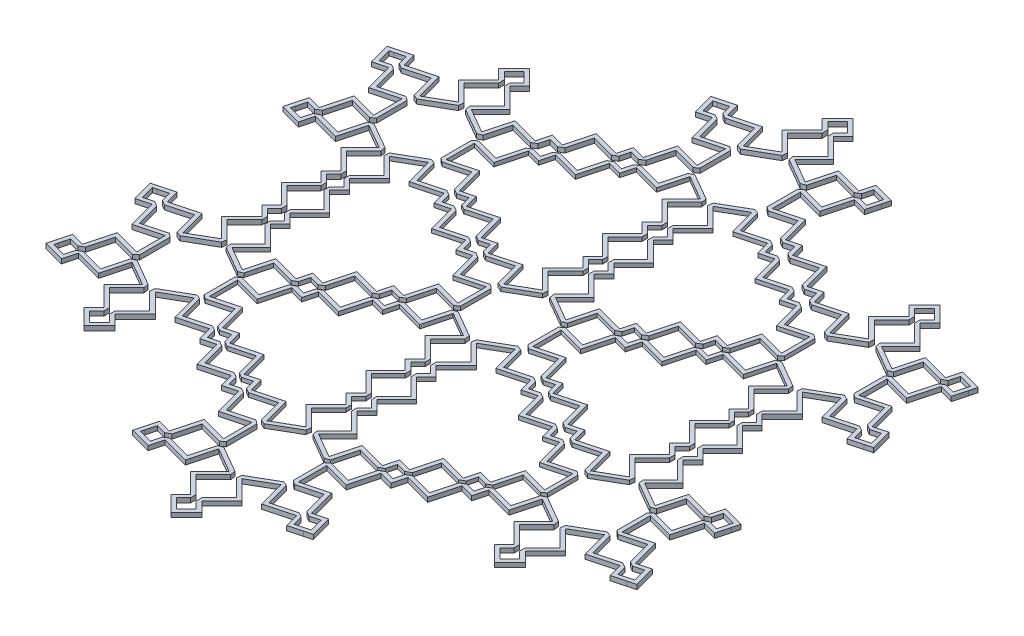
SolidWorks part; units mm, degrees
ref_plane "Front Plane" through (0, 0, 0) normal (0, 0, 1) x (1, 0, 0)
ref_plane "Top Plane" through (0, 0, 0) normal (0, 1, 0) x (1, 0, 0)
ref_plane "Right Plane" through (0, 0, 0) normal (1, 0, 0) x (0, 0, -1)
sketch "Sketch1" plane through (0, 0, 0) normal (0, 1, 0) x (1, 0, 0)
  circle A0 centre (0, 0) radius 261.8
  dimension "D1" = 523.6
extrude "Boss-Extrude1" add sketch "Sketch1" against normal blind 10
sketch "Sketch Scematic" plane through (-2617.9918, 0, 0) normal (0, -1, 0) x (0, 0, 1)
  line L0 (218.165, -2617.9918) -> (0, -2617.9918) construction
  line L5 (370.8825, -2353.4773) -> (676.3175, -2882.5062) construction
  line L6 (218.165, -2617.9918) -> (829.035, -2617.9918) construction
  line L17 (436.3325, -2769.1435) -> (676.3175, -2353.4773) construction
  line L67 (219.0234, -3145.5338) -> (304.5881, -3145.5538)
  line L74 (304.5881, -3145.5538) -> (347.3886, -3071.4366)
  line L75 (347.3886, -3071.4366) -> (304.5846, -2997.3376)
  line L76 (304.5846, -2997.3376) -> (219.02, -2997.3177)
  line L77 (219.02, -2997.3177) -> (176.2194, -3071.4348)
  line L78 (176.2194, -3071.4348) -> (219.0234, -3145.5338)
  line L127 (365.3494, -2981.0558) -> (304.5846, -2997.3376)
  line L128 (288.3027, -2936.5728) -> (304.5846, -2997.3376)
  line L129 (349.0675, -2920.2909) -> (288.3027, -2936.5728)
  line L130 (349.0675, -2920.2909) -> (365.3494, -2981.0558)
  line L132 (341.0827, -2890.4911) -> (349.0675, -2920.2909)
  line L181 (566.3766, -2692.0829) -> (609.1761, -2617.9918)
  line L182 (609.1761, -2617.9918) -> (566.3891, -2543.8668)
  line L183 (566.3891, -2543.8668) -> (480.8154, -2543.8867)
  line L184 (480.8154, -2543.8867) -> (438.0159, -2617.9779)
  line L185 (438.0159, -2617.9779) -> (480.8029, -2692.1029)
  line L186 (480.8029, -2692.1029) -> (566.3766, -2692.0829)
  line L187 (497.0973, -2483.1219) -> (480.8154, -2543.8867)
  line L188 (420.0506, -2527.6049) -> (480.8154, -2543.8867)
  line L189 (436.3325, -2466.84) -> (420.0506, -2527.6049)
  line L190 (436.3325, -2466.84) -> (497.0973, -2483.1219)
  line L191 (406.5327, -2458.8552) -> (436.3325, -2466.84)
  line L192 (436.3325, -2466.84) -> (444.3173, -2437.0402)
  line L193 (414.5175, -2429.0553) -> (444.3173, -2437.0402)
  line L194 (406.5327, -2458.8552) -> (414.5175, -2429.0553)
  line L195 (602.8823, -2437.0388) -> (610.8658, -2466.839)
  line L196 (610.8658, -2466.839) -> (640.666, -2458.8556)
  line L197 (632.6825, -2429.0553) -> (640.666, -2458.8556)
  line L198 (602.8823, -2437.0388) -> (632.6825, -2429.0553)
  line L199 (627.1443, -2527.5915) -> (566.3891, -2543.8668)
  line L200 (550.1142, -2483.1134) -> (566.3891, -2543.8668)
  line L201 (610.8658, -2466.839) -> (550.1142, -2483.1134)
  line L202 (610.8658, -2466.839) -> (627.1443, -2527.5915)
  line L203 (653.6556, -2662.4712) -> (609.1761, -2617.9918)
  line L204 (653.6556, -2573.5123) -> (609.1761, -2617.9918)
  line L205 (698.135, -2617.9918) -> (653.6556, -2573.5123)
  line L206 (698.135, -2617.9918) -> (653.6556, -2662.4712)
  line L207 (550.0917, -2752.8587) -> (566.3766, -2692.0829)
  line L208 (627.1523, -2708.3678) -> (566.3766, -2692.0829)
  line L209 (610.8675, -2769.1435) -> (627.1523, -2708.3678)
  line L210 (610.8675, -2769.1435) -> (550.0917, -2752.8587)
  line L211 (420.0513, -2708.3812) -> (480.8029, -2692.1029)
  line L212 (497.0841, -2752.8652) -> (480.8029, -2692.1029)
  line L213 (436.3325, -2769.1435) -> (497.0841, -2752.8652)
  line L214 (436.3325, -2769.1435) -> (420.0513, -2708.3812)
  line L215 (349.065, -2617.9918) -> (393.5474, -2573.5094)
  line L216 (349.065, -2617.9918) -> (393.5335, -2662.4603)
  line L217 (393.5335, -2662.4603) -> (438.0159, -2617.9779)
  line L218 (393.5474, -2573.5094) -> (438.0159, -2617.9779)
  line L219 (327.25, -2639.8068) -> (305.435, -2617.9918)
  line L220 (327.25, -2639.8068) -> (349.065, -2617.9918)
  line L221 (349.065, -2617.9918) -> (327.25, -2596.1768)
  line L222 (305.435, -2617.9918) -> (327.25, -2596.1768)
  line L223 (444.318, -2798.946) -> (436.3325, -2769.1435)
  line L224 (436.3325, -2769.1435) -> (406.5353, -2777.1277)
  line L225 (414.5208, -2806.9301) -> (406.5353, -2777.1277)
  line L226 (444.318, -2798.946) -> (414.5208, -2806.9301)
  line L227 (640.6673, -2777.1284) -> (610.8675, -2769.1435)
  line L228 (610.8675, -2769.1435) -> (602.8827, -2798.9434)
  line L229 (632.6825, -2806.9282) -> (602.8827, -2798.9434)
  line L230 (640.6673, -2777.1284) -> (632.6825, -2806.9282)
  line L231 (719.9506, -2596.1768) -> (698.135, -2617.9918)
  line L232 (698.135, -2617.9918) -> (719.95, -2639.8068)
  line L233 (741.765, -2617.9918) -> (719.95, -2639.8068)
  line L234 (719.9506, -2596.1768) -> (741.765, -2617.9918)
  line L235 (349.0675, -2920.2909) -> (378.8673, -2912.3061)
  line L236 (370.8825, -2882.5062) -> (378.8673, -2912.3061)
  line L237 (341.0827, -2890.4911) -> (370.8825, -2882.5062)
  line L238 (458.151, -3049.6267) -> (436.335, -3071.4407)
  line L239 (436.335, -3071.4407) -> (458.149, -3093.2567)
  line L240 (479.965, -3071.4427) -> (458.149, -3093.2567)
  line L289 (458.151, -3049.6267) -> (479.965, -3071.4427)
  line L290 (391.8611, -3115.9145) -> (347.3886, -3071.4366)
  line L291 (391.8652, -3026.9655) -> (347.3886, -3071.4366)
  line L293 (436.335, -3071.4407) -> (391.8652, -3026.9655)
  line L294 (436.335, -3071.4407) -> (391.8611, -3115.9145)
  line L343 (288.3074, -3206.3138) -> (304.5881, -3145.5538)
  line L348 (365.3481, -3161.8344) -> (304.5881, -3145.5538)
  line L357 (354.911, -2413.0838) -> (414.5175, -2429.0553)
  line L358 (370.8825, -2353.4773) -> (354.911, -2413.0838)
  line L359 (370.8825, -2353.4773) -> (430.489, -2369.4488)
  line L360 (430.489, -2369.4488) -> (414.5175, -2429.0553)
  line L361 (444.318, -2798.946) -> (436.3325, -2769.1435)
  line L362 (414.5208, -2806.9301) -> (444.318, -2798.946)
  line L363 (414.5208, -2806.9301) -> (406.5353, -2777.1277)
  line L364 (406.5353, -2777.1277) -> (436.3325, -2769.1435)
  line L430 (349.0675, -3222.5944) -> (365.3481, -3161.8344)
  line L431 (349.0675, -3222.5944) -> (288.3074, -3206.3138)
  line L432 (158.2477, -3161.8187) -> (219.0234, -3145.5338)
  line L433 (235.3083, -3206.3096) -> (219.0234, -3145.5338)
  line L434 (174.5325, -3222.5944) -> (235.3083, -3206.3096)
  line L435 (174.5325, -3222.5944) -> (158.2477, -3161.8187)
  line L436 (632.6825, -2429.0553) -> (566.3891, -2543.8668) construction
  line L437 (741.765, -2617.9918) -> (609.1761, -2617.9918) construction
  line L442 (131.7461, -3026.9616) -> (176.2194, -3071.4348)
  line L443 (131.7383, -3115.9159) -> (176.2194, -3071.4348)
  line L464 (218.165, -2617.9918) -> (261.8, -2574.3568)
  line L465 (261.8, -2574.3568) -> (305.435, -2617.9918)
  line L466 (261.8, -2661.6268) -> (305.435, -2617.9918)
  line L467 (218.165, -2617.9918) -> (261.8, -2661.6268)
  line L510 (566.3766, -2692.0829) -> (632.6825, -2806.9282) construction
  line L512 (627.1443, -2527.5915) -> (550.1142, -2483.1134) construction
  line L513 (602.8823, -2437.0388) -> (640.666, -2458.8556) construction
  line L514 (653.6556, -2573.5123) -> (653.6556, -2662.4712) construction
  line L515 (719.95, -2639.8068) -> (719.9506, -2596.1768) construction
  line L516 (627.1523, -2708.3678) -> (550.0917, -2752.8587) construction
  line L517 (602.8827, -2798.9434) -> (640.6673, -2777.1284) construction
  line L518 (420.0506, -2527.6049) -> (497.0973, -2483.1219) construction
  line L519 (444.3173, -2437.0402) -> (406.5327, -2458.8552) construction
  line L520 (354.911, -2413.0838) -> (430.489, -2369.4488) construction
  line L521 (87.265, -3071.4427) -> (131.7383, -3115.9159)
  line L522 (87.265, -3071.4427) -> (131.7461, -3026.9616)
  line L523 (174.5325, -2920.2909) -> (235.2966, -2936.5726)
  line L524 (174.5325, -2920.2909) -> (158.2559, -2981.036)
  line L526 (158.2559, -2981.036) -> (219.02, -2997.3177)
  line L528 (235.2966, -2936.5726) -> (219.02, -2997.3177)
  line L529 (144.7327, -2912.3061) -> (152.7175, -2882.5062)
  line L530 (144.7327, -2912.3061) -> (174.5325, -2920.2909)
  line L531 (174.5325, -2920.2909) -> (182.5173, -2890.4911)
  line L532 (152.7175, -2882.5062) -> (182.5173, -2890.4911)
  line L533 (65.4481, -3093.2596) -> (87.265, -3071.4427)
  line L534 (87.265, -3071.4427) -> (65.4519, -3049.6296)
  line L535 (43.635, -3071.4465) -> (65.4519, -3049.6296)
  line L536 (65.4481, -3093.2596) -> (43.635, -3071.4465)
  line L537 (182.5173, -3252.3943) -> (174.5325, -3222.5944)
  line L538 (174.5325, -3222.5944) -> (144.7327, -3230.5793)
  line L539 (152.7175, -3260.3791) -> (144.7327, -3230.5793)
  line L540 (182.5173, -3252.3943) -> (152.7175, -3260.3791)
  line L541 (378.8676, -3230.5798) -> (349.0675, -3222.5944)
  line L542 (349.0675, -3222.5944) -> (341.0827, -3252.3943)
  line L543 (370.8825, -3260.3791) -> (341.0827, -3252.3943)
  line L544 (378.8676, -3230.5798) -> (370.8825, -3260.3791)
  line L545 (354.911, -2822.8997) -> (370.8825, -2882.5062)
  line L546 (414.5175, -2806.9282) -> (354.911, -2822.8997)
  line L547 (414.5175, -2806.9282) -> (430.489, -2866.5347)
  line L548 (430.489, -2866.5347) -> (370.8825, -2882.5062)
  line L549 (65.4481, -3093.2596) -> (87.265, -3071.4427)
  line L550 (43.635, -3071.4465) -> (65.4481, -3093.2596)
  line L551 (406.5353, -2777.1277) -> (444.318, -2798.946) construction
  line L552 (444.318, -2798.946) -> (406.5353, -2777.1277) construction
  line L553 (497.0841, -2752.8652) -> (420.0513, -2708.3812) construction
  line L554 (261.8, -2574.3568) -> (261.8, -2661.6268) construction
  line L555 (43.635, -3071.4465) -> (65.4519, -3049.6296)
  line L556 (65.4519, -3049.6296) -> (87.265, -3071.4427)
  line L557 (109.0825, -2806.9282) -> (168.689, -2822.8997)
  line L558 (168.689, -2822.8997) -> (152.7175, -2882.5062)
  line L560 (93.111, -2866.5347) -> (152.7175, -2882.5062)
  line L561 (109.0825, -2806.9282) -> (93.111, -2866.5347)
  line L562 (109.0825, -2806.9282) -> (0, -2617.9918) construction
  line L563 (414.5175, -2806.9282) -> (109.0825, -3335.9571) construction
  line L564 (109.0825, -2806.9282) -> (414.5175, -3335.9571) construction
  line L565 (87.265, -3071.4427) -> (567.235, -3071.4427) construction
  line L566 (479.965, -3071.4427) -> (347.3886, -3071.4366) construction
  line L567 (370.8825, -3260.3791) -> (304.5881, -3145.5538) construction
  line L568 (219.0234, -3145.5338) -> (152.7175, -3260.3791) construction
  line L569 (391.8611, -3115.9145) -> (391.8652, -3026.9655) construction
  line L570 (458.151, -3049.6267) -> (458.149, -3093.2567) construction
  line L571 (365.3481, -3161.8344) -> (288.3074, -3206.3138) construction
  line L572 (341.0827, -3252.3943) -> (378.8676, -3230.5798) construction
  line L573 (235.3083, -3206.3096) -> (158.2477, -3161.8187) construction
  line L574 (144.7327, -3230.5793) -> (182.5173, -3252.3943) construction
  line L575 (288.3027, -2936.5728) -> (365.3494, -2981.0558) construction
  line L576 (378.8673, -2912.3061) -> (341.0827, -2890.4911) construction
  line L577 (354.911, -2822.8997) -> (430.489, -2866.5347) construction
  line L578 (65.4519, -3049.6296) -> (65.4481, -3093.2596) construction
  line L579 (65.4481, -3093.2596) -> (65.4519, -3049.6296) construction
  line L580 (131.7383, -3115.9159) -> (131.7461, -3026.9616) construction
  line L581 (168.689, -2822.8997) -> (93.111, -2866.5347) construction
  line L582 (-347.3531, -3071.4427) -> (-304.5881, -3145.5538)
  line L583 (-304.5881, -3145.5538) -> (-219.0004, -3145.5616)
  line L584 (-219.0004, -3145.5616) -> (-176.2309, -3071.4427)
  line L585 (-176.2309, -3071.4427) -> (-218.9959, -2997.3316)
  line L586 (-218.9959, -2997.3316) -> (-304.5835, -2997.3238)
  line L587 (-304.5835, -2997.3238) -> (-347.3531, -3071.4427)
  line L588 (-131.7479, -3115.9256) -> (-176.2309, -3071.4427)
  line L589 (-131.7479, -3026.9597) -> (-176.2309, -3071.4427)
  line L590 (-87.265, -3071.4427) -> (-131.7479, -3026.9597)
  line L591 (-87.265, -3071.4427) -> (-131.7479, -3115.9256)
  line L592 (-65.45, -3049.6277) -> (-87.265, -3071.4427)
  line L593 (-87.265, -3071.4427) -> (-65.45, -3093.2577)
  line L594 (-43.635, -3071.4427) -> (-65.45, -3093.2577)
  line L595 (-65.45, -3049.6277) -> (-43.635, -3071.4427)
  line L596 (-144.7313, -3230.5796) -> (-174.5308, -3222.5934)
  line L597 (-174.5308, -3222.5934) -> (-182.517, -3252.3929)
  line L598 (-152.7175, -3260.3791) -> (-182.517, -3252.3929)
  line L599 (-144.7313, -3230.5796) -> (-152.7175, -3260.3791)
  line L600 (-235.2832, -3206.3149) -> (-219.0004, -3145.5616)
  line L601 (-158.249, -3161.8439) -> (-219.0004, -3145.5616)
  line L602 (-174.5308, -3222.5934) -> (-158.249, -3161.8439)
  line L603 (-174.5308, -3222.5934) -> (-235.2832, -3206.3149)
  line L604 (-365.3481, -3161.8344) -> (-304.5881, -3145.5538)
  line L605 (-288.3074, -3206.3138) -> (-304.5881, -3145.5538)
  line L606 (-349.0675, -3222.5944) -> (-288.3074, -3206.3138)
  line L607 (-349.0675, -3222.5944) -> (-365.3481, -3161.8344)
  line L608 (-391.8441, -3026.9517) -> (-347.3531, -3071.4427)
  line L609 (-391.8441, -3115.9336) -> (-347.3531, -3071.4427)
  line L610 (-436.335, -3071.4427) -> (-391.8441, -3115.9336)
  line L611 (-436.335, -3071.4427) -> (-391.8441, -3026.9517)
  line L612 (-288.3052, -2936.5721) -> (-304.5835, -2997.3238)
  line L613 (-365.3458, -2981.0426) -> (-304.5835, -2997.3238)
  line L614 (-349.0675, -2920.2909) -> (-365.3458, -2981.0426)
  line L615 (-349.0675, -2920.2909) -> (-288.3052, -2936.5721)
  line L616 (-174.5325, -2920.2909) -> (-158.2508, -2981.055)
  line L617 (-174.5325, -2920.2909) -> (-235.2776, -2936.5675)
  line L618 (-235.2776, -2936.5675) -> (-218.9959, -2997.3316)
  line L619 (-158.2508, -2981.055) -> (-218.9959, -2997.3316)
  line L620 (-182.5173, -2890.4911) -> (-152.7175, -2882.5062)
  line L621 (-182.5173, -2890.4911) -> (-174.5325, -2920.2909)
  line L622 (-174.5325, -2920.2909) -> (-144.7327, -2912.3061)
  line L623 (-152.7175, -2882.5062) -> (-144.7327, -2912.3061)
  line L624 (-378.87, -2912.3054) -> (-349.0675, -2920.2909)
  line L625 (-349.0675, -2920.2909) -> (-341.0834, -2890.4937)
  line L626 (-370.8858, -2882.5082) -> (-341.0834, -2890.4937)
  line L627 (-378.87, -2912.3054) -> (-370.8858, -2882.5082)
  line L628 (-458.15, -3093.2577) -> (-436.335, -3071.4427)
  line L629 (-436.335, -3071.4427) -> (-458.15, -3049.6277)
  line L630 (-479.965, -3071.4427) -> (-458.15, -3049.6277)
  line L631 (-458.15, -3093.2577) -> (-479.965, -3071.4427)
  line L632 (-341.0829, -3252.3948) -> (-349.0675, -3222.5944)
  line L633 (-349.0675, -3222.5944) -> (-378.8673, -3230.5793)
  line L634 (-370.8825, -3260.3791) -> (-378.8673, -3230.5793)
  line L635 (-341.0829, -3252.3948) -> (-370.8825, -3260.3791)
  line L636 (0, -3027.8077) -> (-43.635, -3071.4427)
  line L637 (43.635, -3071.4427) -> (0, -3027.8077)
  line L638 (43.635, -3071.4427) -> (0, -3115.0777)
  line L639 (0, -3115.0777) -> (-43.635, -3071.4427)
  line L640 (-378.87, -2912.3054) -> (-349.0675, -2920.2909)
  line L641 (-370.8858, -2882.5082) -> (-378.87, -2912.3054)
  line L642 (-370.8858, -2882.5082) -> (-341.0834, -2890.4937)
  line L643 (-341.0834, -2890.4937) -> (-349.0675, -2920.2909)
  line L644 (-109.0825, -2806.9282) -> (-93.111, -2866.5347)
  line L645 (-93.111, -2866.5347) -> (-152.7175, -2882.5062)
  line L646 (-168.689, -2822.8997) -> (-152.7175, -2882.5062)
  line L647 (-109.0825, -2806.9282) -> (-168.689, -2822.8997)
  line L648 (-109.0825, -2806.9282) -> (0, -2617.9918) construction
  line L649 (43.635, -3071.4427) -> (-567.235, -3071.4427) construction
  line L650 (-109.0825, -2806.9282) -> (-414.5175, -3335.9571) construction
  line L651 (-349.0675, -2920.2909) -> (-109.0825, -3335.9571) construction
  line L652 (-152.7175, -3260.3791) -> (-219.0004, -3145.5616) construction
  line L653 (-370.8825, -3260.3791) -> (-304.5881, -3145.5538) construction
  line L654 (-347.3531, -3071.4427) -> (-479.965, -3071.4427) construction
  line L655 (-235.2832, -3206.3149) -> (-158.249, -3161.8439) construction
  line L656 (-144.7313, -3230.5796) -> (-182.517, -3252.3929) construction
  line L657 (-288.3074, -3206.3138) -> (-365.3481, -3161.8344) construction
  line L658 (-378.8673, -3230.5793) -> (-341.0829, -3252.3948) construction
  line L659 (-391.8441, -3115.9336) -> (-391.8441, -3026.9517) construction
  line L660 (-458.15, -3049.6277) -> (-458.15, -3093.2577) construction
  line L661 (-131.7479, -3026.9597) -> (-131.7479, -3115.9256) construction
  line L662 (-65.45, -3093.2577) -> (-65.45, -3049.6277) construction
  line L663 (0, -3027.8077) -> (0, -3115.0777) construction
  line L664 (-341.0834, -2890.4937) -> (-378.87, -2912.3054) construction
  line L665 (-378.87, -2912.3054) -> (-341.0834, -2890.4937) construction
  line L666 (-365.3458, -2981.0426) -> (-288.3052, -2936.5721) construction
  line L667 (-93.111, -2866.5347) -> (-168.689, -2822.8997) construction
  line L668 (-566.3766, -2543.9006) -> (-609.1761, -2617.9918)
  line L669 (-609.1761, -2617.9918) -> (-566.3891, -2692.1167)
  line L670 (-566.3891, -2692.1167) -> (-480.8154, -2692.0968)
  line L671 (-480.8154, -2692.0968) -> (-438.0159, -2618.0057)
  line L672 (-438.0159, -2618.0057) -> (-480.8029, -2543.8807)
  line L673 (-480.8029, -2543.8807) -> (-566.3766, -2543.9006)
  line L674 (-497.0973, -2752.8616) -> (-480.8154, -2692.0968)
  line L675 (-420.0506, -2708.3787) -> (-480.8154, -2692.0968)
  line L676 (-436.3325, -2769.1435) -> (-420.0506, -2708.3787)
  line L677 (-436.3325, -2769.1435) -> (-497.0973, -2752.8616)
  line L678 (-406.5327, -2777.1284) -> (-436.3325, -2769.1435)
  line L679 (-436.3325, -2769.1435) -> (-444.3173, -2798.9434)
  line L680 (-414.5175, -2806.9282) -> (-444.3173, -2798.9434)
  line L681 (-406.5327, -2777.1284) -> (-414.5175, -2806.9282)
  line L682 (-602.8823, -2798.9447) -> (-610.8658, -2769.1445)
  line L683 (-610.8658, -2769.1445) -> (-640.666, -2777.128)
  line L684 (-632.6825, -2806.9282) -> (-640.666, -2777.128)
  line L685 (-602.8823, -2798.9447) -> (-632.6825, -2806.9282)
  line L686 (-627.1443, -2708.3921) -> (-566.3891, -2692.1167)
  line L687 (-550.1142, -2752.8701) -> (-566.3891, -2692.1167)
  line L688 (-610.8658, -2769.1445) -> (-550.1142, -2752.8701)
  line L689 (-610.8658, -2769.1445) -> (-627.1443, -2708.3921)
  line L690 (-653.6556, -2573.5123) -> (-609.1761, -2617.9918)
  line L691 (-653.6556, -2662.4712) -> (-609.1761, -2617.9918)
  line L692 (-698.135, -2617.9918) -> (-653.6556, -2662.4712)
  line L693 (-698.135, -2617.9918) -> (-653.6556, -2573.5123)
  line L694 (-550.0917, -2483.1249) -> (-566.3766, -2543.9006)
  line L695 (-627.1523, -2527.6158) -> (-566.3766, -2543.9006)
  line L696 (-610.8675, -2466.84) -> (-627.1523, -2527.6158)
  line L697 (-610.8675, -2466.84) -> (-550.0917, -2483.1249)
  line L698 (-420.0513, -2527.6023) -> (-480.8029, -2543.8807)
  line L699 (-497.0841, -2483.1184) -> (-480.8029, -2543.8807)
  line L700 (-436.3325, -2466.84) -> (-497.0841, -2483.1184)
  line L701 (-436.3325, -2466.84) -> (-420.0513, -2527.6023)
  line L702 (-349.065, -2617.9918) -> (-393.5474, -2662.4742)
  line L703 (-349.065, -2617.9918) -> (-393.5335, -2573.5233)
  line L704 (-393.5335, -2573.5233) -> (-438.0159, -2618.0057)
  line L705 (-393.5474, -2662.4742) -> (-438.0159, -2618.0057)
  line L706 (-327.25, -2596.1768) -> (-305.435, -2617.9918)
  line L707 (-327.25, -2596.1768) -> (-349.065, -2617.9918)
  line L708 (-349.065, -2617.9918) -> (-327.25, -2639.8068)
  line L709 (-305.435, -2617.9918) -> (-327.25, -2639.8068)
  line L710 (-444.318, -2437.0376) -> (-436.3325, -2466.84)
  line L711 (-436.3325, -2466.84) -> (-406.5353, -2458.8559)
  line L712 (-414.5208, -2429.0534) -> (-406.5353, -2458.8559)
  line L713 (-444.318, -2437.0376) -> (-414.5208, -2429.0534)
  line L714 (-640.6673, -2458.8552) -> (-610.8675, -2466.84)
  line L715 (-610.8675, -2466.84) -> (-602.8827, -2437.0402)
  line L716 (-632.6825, -2429.0553) -> (-602.8827, -2437.0402)
  line L717 (-640.6673, -2458.8552) -> (-632.6825, -2429.0553)
  line L718 (-719.9506, -2639.8068) -> (-698.135, -2617.9918)
  line L719 (-698.135, -2617.9918) -> (-719.95, -2596.1768)
  line L720 (-741.765, -2617.9918) -> (-719.95, -2596.1768)
  line L721 (-719.9506, -2639.8068) -> (-741.765, -2617.9918)
  line L722 (-354.911, -2822.8997) -> (-414.5175, -2806.9282)
  line L723 (-370.8825, -2882.5062) -> (-354.911, -2822.8997)
  line L724 (-370.8825, -2882.5062) -> (-430.489, -2866.5347)
  line L725 (-430.489, -2866.5347) -> (-414.5175, -2806.9282)
  line L726 (-444.318, -2437.0376) -> (-436.3325, -2466.84)
  line L727 (-414.5208, -2429.0534) -> (-444.318, -2437.0376)
  line L728 (-414.5208, -2429.0534) -> (-406.5353, -2458.8559)
  line L729 (-406.5353, -2458.8559) -> (-436.3325, -2466.84)
  line L730 (-218.165, -2617.9918) -> (-261.8, -2661.6268)
  line L731 (-261.8, -2661.6268) -> (-305.435, -2617.9918)
  line L732 (-261.8, -2574.3568) -> (-305.435, -2617.9918)
  line L733 (-218.165, -2617.9918) -> (-261.8, -2574.3568)
  line L734 (-218.165, -2617.9918) -> (0, -2617.9918) construction
  line L735 (-370.8825, -2882.5062) -> (-676.3175, -2353.4773) construction
  line L736 (-218.165, -2617.9918) -> (-829.035, -2617.9918) construction
  line L737 (-436.3325, -2466.84) -> (-676.3175, -2882.5062) construction
  line L738 (-632.6825, -2806.9282) -> (-566.3891, -2692.1167) construction
  line L739 (-741.765, -2617.9918) -> (-609.1761, -2617.9918) construction
  line L740 (-566.3766, -2543.9006) -> (-632.6825, -2429.0553) construction
  line L741 (-627.1443, -2708.3921) -> (-550.1142, -2752.8701) construction
  line L742 (-602.8823, -2798.9447) -> (-640.666, -2777.128) construction
  line L743 (-653.6556, -2662.4712) -> (-653.6556, -2573.5123) construction
  line L744 (-719.95, -2596.1768) -> (-719.9506, -2639.8068) construction
  line L745 (-627.1523, -2527.6158) -> (-550.0917, -2483.1249) construction
  line L746 (-602.8827, -2437.0402) -> (-640.6673, -2458.8552) construction
  line L747 (-420.0506, -2708.3787) -> (-497.0973, -2752.8616) construction
  line L748 (-444.3173, -2798.9434) -> (-406.5327, -2777.1284) construction
  line L749 (-354.911, -2822.8997) -> (-430.489, -2866.5347) construction
  line L750 (-406.5353, -2458.8559) -> (-444.318, -2437.0376) construction
  line L751 (-444.318, -2437.0376) -> (-406.5353, -2458.8559) construction
  line L752 (-497.0841, -2483.1184) -> (-420.0513, -2527.6023) construction
  line L753 (-261.8, -2661.6268) -> (-261.8, -2574.3568) construction
  line L754 (-219.0234, -2090.4497) -> (-304.5881, -2090.4298)
  line L755 (-304.5881, -2090.4298) -> (-347.3886, -2164.5469)
  line L756 (-347.3886, -2164.5469) -> (-304.5846, -2238.6459)
  line L757 (-304.5846, -2238.6459) -> (-219.02, -2238.6658)
  line L758 (-219.02, -2238.6658) -> (-176.2194, -2164.5487)
  line L759 (-176.2194, -2164.5487) -> (-219.0234, -2090.4497)
  line L760 (-365.3494, -2254.9278) -> (-304.5846, -2238.6459)
  line L761 (-288.3027, -2299.4107) -> (-304.5846, -2238.6459)
  line L762 (-349.0675, -2315.6926) -> (-288.3027, -2299.4107)
  line L763 (-349.0675, -2315.6926) -> (-365.3494, -2254.9278)
  line L764 (-341.0827, -2345.4925) -> (-349.0675, -2315.6926)
  line L765 (-349.0675, -2315.6926) -> (-378.8673, -2323.6775)
  line L766 (-370.8825, -2353.4773) -> (-378.8673, -2323.6775)
  line L767 (-341.0827, -2345.4925) -> (-370.8825, -2353.4773)
  line L768 (-458.151, -2186.3569) -> (-436.335, -2164.5429)
  line L769 (-436.335, -2164.5429) -> (-458.149, -2142.7269)
  line L770 (-479.965, -2164.5409) -> (-458.149, -2142.7269)
  line L771 (-458.151, -2186.3569) -> (-479.965, -2164.5409)
  line L772 (-391.8611, -2120.069) -> (-347.3886, -2164.5469)
  line L773 (-391.8652, -2209.0181) -> (-347.3886, -2164.5469)
  line L774 (-436.335, -2164.5429) -> (-391.8652, -2209.0181)
  line L775 (-436.335, -2164.5429) -> (-391.8611, -2120.069)
  line L776 (-288.3074, -2029.6697) -> (-304.5881, -2090.4298)
  line L777 (-365.3481, -2074.1492) -> (-304.5881, -2090.4298)
  line L778 (-349.0675, -2013.3891) -> (-365.3481, -2074.1492)
  line L779 (-349.0675, -2013.3891) -> (-288.3074, -2029.6697)
  line L780 (-158.2477, -2074.1649) -> (-219.0234, -2090.4497)
  line L781 (-235.3083, -2029.674) -> (-219.0234, -2090.4497)
  line L782 (-174.5325, -2013.3891) -> (-235.3083, -2029.674)
  line L783 (-174.5325, -2013.3891) -> (-158.2477, -2074.1649)
  line L784 (-131.7461, -2209.022) -> (-176.2194, -2164.5487)
  line L785 (-131.7383, -2120.0676) -> (-176.2194, -2164.5487)
  line L786 (-87.265, -2164.5409) -> (-131.7383, -2120.0676)
  line L787 (-87.265, -2164.5409) -> (-131.7461, -2209.022)
  line L788 (-174.5325, -2315.6926) -> (-235.2966, -2299.4109)
  line L789 (-174.5325, -2315.6926) -> (-158.2559, -2254.9475)
  line L790 (-158.2559, -2254.9475) -> (-219.02, -2238.6658)
  line L791 (-235.2966, -2299.4109) -> (-219.02, -2238.6658)
  line L792 (-144.7327, -2323.6775) -> (-152.7175, -2353.4773)
  line L793 (-144.7327, -2323.6775) -> (-174.5325, -2315.6926)
  line L794 (-174.5325, -2315.6926) -> (-182.5173, -2345.4925)
  line L795 (-152.7175, -2353.4773) -> (-182.5173, -2345.4925)
  line L796 (-65.4481, -2142.724) -> (-87.265, -2164.5409)
  line L797 (-87.265, -2164.5409) -> (-65.4519, -2186.354)
  line L798 (-43.635, -2164.537) -> (-65.4519, -2186.354)
  line L799 (-65.4481, -2142.724) -> (-43.635, -2164.537)
  line L800 (-182.5173, -1983.5893) -> (-174.5325, -2013.3891)
  line L801 (-174.5325, -2013.3891) -> (-144.7327, -2005.4043)
  line L802 (-152.7175, -1975.6044) -> (-144.7327, -2005.4043)
  line L803 (-182.5173, -1983.5893) -> (-152.7175, -1975.6044)
  line L804 (-378.8676, -2005.4038) -> (-349.0675, -2013.3891)
  line L805 (-349.0675, -2013.3891) -> (-341.0827, -1983.5893)
  line L806 (-370.8825, -1975.6044) -> (-341.0827, -1983.5893)
  line L807 (-378.8676, -2005.4038) -> (-370.8825, -1975.6044)
  line L808 (-354.911, -2413.0838) -> (-370.8825, -2353.4773)
  line L809 (-414.5175, -2429.0553) -> (-354.911, -2413.0838)
  line L810 (-414.5175, -2429.0553) -> (-430.489, -2369.4488)
  line L811 (-430.489, -2369.4488) -> (-370.8825, -2353.4773)
  line L812 (-65.4481, -2142.724) -> (-87.265, -2164.5409)
  line L813 (-43.635, -2164.537) -> (-65.4481, -2142.724)
  line L814 (-43.635, -2164.537) -> (-65.4519, -2186.354)
  line L815 (-65.4519, -2186.354) -> (-87.265, -2164.5409)
  line L816 (-109.0825, -2429.0553) -> (-168.689, -2413.0838)
  line L817 (-168.689, -2413.0838) -> (-152.7175, -2353.4773)
  line L818 (-93.111, -2369.4488) -> (-152.7175, -2353.4773)
  line L819 (-109.0825, -2429.0553) -> (-93.111, -2369.4488)
  line L820 (-109.0825, -2429.0553) -> (0, -2617.9918) construction
  line L821 (-414.5175, -2429.0553) -> (-109.0825, -1900.0264) construction
  line L822 (-109.0825, -2429.0553) -> (-414.5175, -1900.0264) construction
  line L823 (-87.265, -2164.5409) -> (-567.235, -2164.5409) construction
  line L824 (-479.965, -2164.5409) -> (-347.3886, -2164.5469) construction
  line L825 (-370.8825, -1975.6044) -> (-304.5881, -2090.4298) construction
  line L826 (-219.0234, -2090.4497) -> (-152.7175, -1975.6044) construction
  line L827 (-391.8611, -2120.069) -> (-391.8652, -2209.0181) construction
  line L828 (-458.151, -2186.3569) -> (-458.149, -2142.7269) construction
  line L829 (-365.3481, -2074.1492) -> (-288.3074, -2029.6697) construction
  line L830 (-341.0827, -1983.5893) -> (-378.8676, -2005.4038) construction
  line L831 (-235.3083, -2029.674) -> (-158.2477, -2074.1649) construction
  line L832 (-144.7327, -2005.4043) -> (-182.5173, -1983.5893) construction
  line L833 (-288.3027, -2299.4107) -> (-365.3494, -2254.9278) construction
  line L834 (-378.8673, -2323.6775) -> (-341.0827, -2345.4925) construction
  line L835 (-354.911, -2413.0838) -> (-430.489, -2369.4488) construction
  line L836 (-65.4519, -2186.354) -> (-65.4481, -2142.724) construction
  line L837 (-65.4481, -2142.724) -> (-65.4519, -2186.354) construction
  line L838 (-131.7383, -2120.0676) -> (-131.7461, -2209.022) construction
  line L839 (-168.689, -2413.0838) -> (-93.111, -2369.4488) construction
  line L840 (347.3531, -2164.5409) -> (304.5881, -2090.4298)
  line L841 (304.5881, -2090.4298) -> (219.0004, -2090.422)
  line L842 (219.0004, -2090.422) -> (176.2309, -2164.5409)
  line L843 (176.2309, -2164.5409) -> (218.9959, -2238.652)
  line L844 (218.9959, -2238.652) -> (304.5835, -2238.6598)
  line L845 (304.5835, -2238.6598) -> (347.3531, -2164.5409)
  line L846 (131.7479, -2120.0579) -> (176.2309, -2164.5409)
  line L847 (131.7479, -2209.0238) -> (176.2309, -2164.5409)
  line L848 (87.265, -2164.5409) -> (131.7479, -2209.0238)
  line L849 (87.265, -2164.5409) -> (131.7479, -2120.0579)
  line L850 (65.45, -2186.3559) -> (87.265, -2164.5409)
  line L851 (87.265, -2164.5409) -> (65.45, -2142.7259)
  line L852 (43.635, -2164.5409) -> (65.45, -2142.7259)
  line L853 (65.45, -2186.3559) -> (43.635, -2164.5409)
  line L854 (144.7313, -2005.4039) -> (174.5308, -2013.3901)
  line L855 (174.5308, -2013.3901) -> (182.517, -1983.5906)
  line L856 (152.7175, -1975.6044) -> (182.517, -1983.5906)
  line L857 (144.7313, -2005.4039) -> (152.7175, -1975.6044)
  line L858 (235.2832, -2029.6687) -> (219.0004, -2090.422)
  line L859 (158.249, -2074.1397) -> (219.0004, -2090.422)
  line L860 (174.5308, -2013.3901) -> (158.249, -2074.1397)
  line L861 (174.5308, -2013.3901) -> (235.2832, -2029.6687)
  line L862 (365.3481, -2074.1492) -> (304.5881, -2090.4298)
  line L863 (288.3074, -2029.6697) -> (304.5881, -2090.4298)
  line L864 (349.0675, -2013.3891) -> (288.3074, -2029.6697)
  line L865 (349.0675, -2013.3891) -> (365.3481, -2074.1492)
  line L866 (391.8441, -2209.0318) -> (347.3531, -2164.5409)
  line L867 (391.8441, -2120.0499) -> (347.3531, -2164.5409)
  line L868 (436.335, -2164.5409) -> (391.8441, -2120.0499)
  line L869 (436.335, -2164.5409) -> (391.8441, -2209.0318)
  line L870 (288.3052, -2299.4114) -> (304.5835, -2238.6598)
  line L871 (365.3458, -2254.941) -> (304.5835, -2238.6598)
  line L872 (349.0675, -2315.6926) -> (365.3458, -2254.941)
  line L873 (349.0675, -2315.6926) -> (288.3052, -2299.4114)
  line L874 (174.5325, -2315.6926) -> (158.2508, -2254.9286)
  line L875 (174.5325, -2315.6926) -> (235.2776, -2299.416)
  line L876 (235.2776, -2299.416) -> (218.9959, -2238.652)
  line L877 (158.2508, -2254.9286) -> (218.9959, -2238.652)
  line L878 (182.5173, -2345.4925) -> (152.7175, -2353.4773)
  line L879 (182.5173, -2345.4925) -> (174.5325, -2315.6926)
  line L880 (174.5325, -2315.6926) -> (144.7327, -2323.6775)
  line L881 (152.7175, -2353.4773) -> (144.7327, -2323.6775)
  line L882 (378.87, -2323.6782) -> (349.0675, -2315.6926)
  line L883 (349.0675, -2315.6926) -> (341.0834, -2345.4898)
  line L884 (370.8858, -2353.4754) -> (341.0834, -2345.4898)
  line L885 (378.87, -2323.6782) -> (370.8858, -2353.4754)
  line L886 (458.15, -2142.7259) -> (436.335, -2164.5409)
  line L887 (436.335, -2164.5409) -> (458.15, -2186.3559)
  line L888 (479.965, -2164.5409) -> (458.15, -2186.3559)
  line L889 (458.15, -2142.7259) -> (479.965, -2164.5409)
  line L890 (341.0829, -1983.5888) -> (349.0675, -2013.3891)
  line L891 (349.0675, -2013.3891) -> (378.8673, -2005.4043)
  line L892 (370.8825, -1975.6044) -> (378.8673, -2005.4043)
  line L893 (341.0829, -1983.5888) -> (370.8825, -1975.6044)
  line L894 (0, -2208.1759) -> (43.635, -2164.5409)
  line L895 (-43.635, -2164.5409) -> (0, -2208.1759)
  line L896 (-43.635, -2164.5409) -> (0, -2120.9059)
  line L897 (0, -2120.9059) -> (43.635, -2164.5409)
  line L898 (378.87, -2323.6782) -> (349.0675, -2315.6926)
  line L899 (370.8858, -2353.4754) -> (378.87, -2323.6782)
  line L900 (370.8858, -2353.4754) -> (341.0834, -2345.4898)
  line L901 (341.0834, -2345.4898) -> (349.0675, -2315.6926)
  line L902 (109.0825, -2429.0553) -> (93.111, -2369.4488)
  line L903 (93.111, -2369.4488) -> (152.7175, -2353.4773)
  line L904 (168.689, -2413.0838) -> (152.7175, -2353.4773)
  line L905 (109.0825, -2429.0553) -> (168.689, -2413.0838)
  line L906 (109.0825, -2429.0553) -> (0, -2617.9918) construction
  line L907 (-43.635, -2164.5409) -> (567.235, -2164.5409) construction
  line L908 (109.0825, -2429.0553) -> (414.5175, -1900.0264) construction
  line L909 (349.0675, -2315.6926) -> (109.0825, -1900.0264) construction
  line L910 (152.7175, -1975.6044) -> (219.0004, -2090.422) construction
  line L911 (370.8825, -1975.6044) -> (304.5881, -2090.4298) construction
  line L912 (347.3531, -2164.5409) -> (479.965, -2164.5409) construction
  line L913 (235.2832, -2029.6687) -> (158.249, -2074.1397) construction
  line L914 (144.7313, -2005.4039) -> (182.517, -1983.5906) construction
  line L915 (288.3074, -2029.6697) -> (365.3481, -2074.1492) construction
  line L916 (378.8673, -2005.4043) -> (341.0829, -1983.5888) construction
  line L917 (391.8441, -2120.0499) -> (391.8441, -2209.0318) construction
  line L918 (458.15, -2186.3559) -> (458.15, -2142.7259) construction
  line L919 (131.7479, -2209.0238) -> (131.7479, -2120.0579) construction
  line L920 (65.45, -2142.7259) -> (65.45, -2186.3559) construction
  line L921 (0, -2208.1759) -> (0, -2120.9059) construction
  line L922 (341.0834, -2345.4898) -> (378.87, -2323.6782) construction
  line L923 (378.87, -2323.6782) -> (341.0834, -2345.4898) construction
  line L924 (365.3458, -2254.941) -> (288.3052, -2299.4114) construction
  line L925 (93.111, -2369.4488) -> (168.689, -2413.0838) construction
  line L926 (42.7766, -2692.0829) -> (85.5761, -2617.9918)
  line L927 (85.5761, -2617.9918) -> (42.7891, -2543.8668)
  line L928 (42.7891, -2543.8668) -> (-42.7846, -2543.8867)
  line L929 (-42.7846, -2543.8867) -> (-85.5841, -2617.9779)
  line L930 (-85.5841, -2617.9779) -> (-42.7971, -2692.1029)
  line L931 (-42.7971, -2692.1029) -> (42.7766, -2692.0829)
  line L932 (-26.5027, -2483.1219) -> (-42.7846, -2543.8867)
  line L933 (-103.5494, -2527.6049) -> (-42.7846, -2543.8867)
  line L934 (-87.2675, -2466.84) -> (-103.5494, -2527.6049)
  line L935 (-87.2675, -2466.84) -> (-26.5027, -2483.1219)
  line L936 (-117.0673, -2458.8552) -> (-87.2675, -2466.84)
  line L937 (-87.2675, -2466.84) -> (-79.2827, -2437.0402)
  line L938 (-109.0825, -2429.0553) -> (-79.2827, -2437.0402)
  line L939 (-117.0673, -2458.8552) -> (-109.0825, -2429.0553)
  line L940 (79.2823, -2437.0388) -> (87.2658, -2466.839)
  line L941 (87.2658, -2466.839) -> (117.066, -2458.8556)
  line L942 (109.0825, -2429.0553) -> (117.066, -2458.8556)
  line L943 (79.2823, -2437.0388) -> (109.0825, -2429.0553)
  line L944 (103.5443, -2527.5915) -> (42.7891, -2543.8668)
  line L945 (26.5142, -2483.1134) -> (42.7891, -2543.8668)
  line L946 (87.2658, -2466.839) -> (26.5142, -2483.1134)
  line L947 (87.2658, -2466.839) -> (103.5443, -2527.5915)
  line L948 (130.0556, -2662.4712) -> (85.5761, -2617.9918)
  line L949 (130.0556, -2573.5123) -> (85.5761, -2617.9918)
  line L950 (174.535, -2617.9918) -> (130.0556, -2573.5123)
  line L951 (174.535, -2617.9918) -> (130.0556, -2662.4712)
  line L952 (26.4917, -2752.8587) -> (42.7766, -2692.0829)
  line L953 (103.5523, -2708.3678) -> (42.7766, -2692.0829)
  line L954 (87.2675, -2769.1435) -> (103.5523, -2708.3678)
  line L955 (87.2675, -2769.1435) -> (26.4917, -2752.8587)
  line L956 (-103.5487, -2708.3812) -> (-42.7971, -2692.1029)
  line L957 (-26.5159, -2752.8652) -> (-42.7971, -2692.1029)
  line L958 (-87.2675, -2769.1435) -> (-26.5159, -2752.8652)
  line L959 (-87.2675, -2769.1435) -> (-103.5487, -2708.3812)
  line L960 (-174.535, -2617.9918) -> (-130.0526, -2573.5094)
  line L961 (-174.535, -2617.9918) -> (-130.0665, -2662.4603)
  line L962 (-130.0665, -2662.4603) -> (-85.5841, -2617.9779)
  line L963 (-130.0526, -2573.5094) -> (-85.5841, -2617.9779)
  line L964 (-196.35, -2639.8068) -> (-218.165, -2617.9918)
  line L965 (-196.35, -2639.8068) -> (-174.535, -2617.9918)
  line L966 (-174.535, -2617.9918) -> (-196.35, -2596.1768)
  line L967 (-218.165, -2617.9918) -> (-196.35, -2596.1768)
  line L968 (-79.282, -2798.946) -> (-87.2675, -2769.1435)
  line L969 (-87.2675, -2769.1435) -> (-117.0647, -2777.1277)
  line L970 (-109.0792, -2806.9301) -> (-117.0647, -2777.1277)
  line L971 (-79.282, -2798.946) -> (-109.0792, -2806.9301)
  line L972 (117.0673, -2777.1284) -> (87.2675, -2769.1435)
  line L973 (87.2675, -2769.1435) -> (79.2827, -2798.9434)
  line L974 (109.0825, -2806.9282) -> (79.2827, -2798.9434)
  line L975 (117.0673, -2777.1284) -> (109.0825, -2806.9282)
  line L976 (196.3506, -2596.1768) -> (174.535, -2617.9918)
  line L977 (174.535, -2617.9918) -> (196.35, -2639.8068)
  line L978 (218.165, -2617.9918) -> (196.35, -2639.8068)
  line L979 (196.3506, -2596.1768) -> (218.165, -2617.9918)
  line L980 (-168.689, -2413.0838) -> (-109.0825, -2429.0553)
  line L981 (-152.7175, -2353.4773) -> (-168.689, -2413.0838)
  line L982 (-152.7175, -2353.4773) -> (-93.111, -2369.4488)
  line L983 (-93.111, -2369.4488) -> (-109.0825, -2429.0553)
  line L984 (-79.282, -2798.946) -> (-87.2675, -2769.1435)
  line L985 (-109.0792, -2806.9301) -> (-79.282, -2798.946)
  line L986 (-109.0792, -2806.9301) -> (-117.0647, -2777.1277)
  line L987 (-117.0647, -2777.1277) -> (-87.2675, -2769.1435)
  line L988 (-305.435, -2617.9918) -> (-261.8, -2574.3568)
  line L989 (-261.8, -2574.3568) -> (-218.165, -2617.9918)
  line L990 (-261.8, -2661.6268) -> (-218.165, -2617.9918)
  line L991 (-305.435, -2617.9918) -> (-261.8, -2661.6268)
  line L992 (-305.435, -2617.9918) -> (-523.6, -2617.9918) construction
  line L993 (-152.7175, -2353.4773) -> (152.7175, -2882.5062) construction
  line L994 (-305.435, -2617.9918) -> (305.435, -2617.9918) construction
  line L995 (-87.2675, -2769.1435) -> (152.7175, -2353.4773) construction
  line L996 (109.0825, -2429.0553) -> (42.7891, -2543.8668) construction
  line L997 (218.165, -2617.9918) -> (85.5761, -2617.9918) construction
  line L998 (42.7766, -2692.0829) -> (109.0825, -2806.9282) construction
  line L999 (103.5443, -2527.5915) -> (26.5142, -2483.1134) construction
  line L1000 (79.2823, -2437.0388) -> (117.066, -2458.8556) construction
  line L1001 (130.0556, -2573.5123) -> (130.0556, -2662.4712) construction
  line L1002 (196.35, -2639.8068) -> (196.3506, -2596.1768) construction
  line L1003 (103.5523, -2708.3678) -> (26.4917, -2752.8587) construction
  line L1004 (79.2827, -2798.9434) -> (117.0673, -2777.1284) construction
  line L1005 (-103.5494, -2527.6049) -> (-26.5027, -2483.1219) construction
  line L1006 (-79.2827, -2437.0402) -> (-117.0673, -2458.8552) construction
  line L1007 (-168.689, -2413.0838) -> (-93.111, -2369.4488) construction
  line L1008 (-117.0647, -2777.1277) -> (-79.282, -2798.946) construction
  line L1009 (-79.282, -2798.946) -> (-117.0647, -2777.1277) construction
  line L1010 (-26.5159, -2752.8652) -> (-103.5487, -2708.3812) construction
  line L1011 (-261.8, -2574.3568) -> (-261.8, -2661.6268) construction
  circle A7 centre (261.8, -3071.4427) radius 218.165
  circle A8 centre (261.8, -3071.4427) radius 174.535
  circle A9 centre (261.8, -3071.4427) radius 305.435
  circle A10 centre (523.6, -2617.9918) radius 74.115 construction
  circle A11 centre (261.8, -3071.4427) radius 74.115 construction
  circle A12 centre (-261.8, -3071.4427) radius 218.165
  circle A13 centre (-261.8, -3071.4427) radius 174.535
  circle A15 centre (523.6, -2617.9918) radius 218.165
  circle A18 centre (523.6, -2617.9918) radius 174.535
  circle A30 centre (523.6, -2617.9918) radius 305.435
  circle A31 centre (-261.8, -3071.4427) radius 305.435
  circle A32 centre (-261.8, -3071.4427) radius 74.115 construction
  circle A33 centre (-523.6, -2617.9918) radius 218.165
  circle A34 centre (-523.6, -2617.9918) radius 174.535
  circle A35 centre (-523.6, -2617.9918) radius 305.435
  circle A36 centre (-523.6, -2617.9918) radius 74.115 construction
  circle A37 centre (-261.8, -2164.5409) radius 218.165
  circle A38 centre (-261.8, -2164.5409) radius 174.535
  circle A39 centre (-261.8, -2164.5409) radius 305.435
  circle A40 centre (-261.8, -2164.5409) radius 74.115 construction
  circle A41 centre (261.8, -2164.5409) radius 218.165
  circle A42 centre (261.8, -2164.5409) radius 174.535
  circle A43 centre (261.8, -2164.5409) radius 305.435
  circle A44 centre (261.8, -2164.5409) radius 74.115 construction
  circle A45 centre (0, -2617.9918) radius 218.165
  circle A46 centre (0, -2617.9918) radius 174.535
  circle A47 centre (0, -2617.9918) radius 305.435
  circle A48 centre (0, -2617.9918) radius 74.115 construction
  circle A49 centre (0, -2617.9918) radius 21.815
  point P1 (0, 0)
  point P122 (0, 0)
  point P371 (-288.3105, -3035.76)
  point P372 (0, 0)
  dimension "D2" = 436.33
  dimension "D1" = 610.87
  dimension "D3" = 349.07
  dimension "D4" = 148.23
  dimension "D5" = 523.6
  dimension "D6" = 148.23
  dimension "D7" = 45
  dimension "D8" = 45
  dimension "D9" = 45
  dimension "D10" = 45
  dimension "D11" = 45
  dimension "D13" = 45
  dimension "D14" = 45
  dimension "D16" = 45
  dimension "D17" = 45
  dimension "D18" = 2
  dimension "D19" = 45
  dimension "D20" = 45
  dimension "D21" = 45
  dimension "D22" = 45
  dimension "D25" = 60
  dimension "D26" = 60
  dimension "D27" = 6
  dimension "D28" = 90
  dimension "D29" = 90
sketch "Sketch25" plane through (7832.1782, 0, 0) normal (0, -1, 0) x (0, 0, 1)
  line L0 (47.2925, 7765.9046) -> (81.0608, 7824.3616)
  line L1 (56.013, 7763.568) -> (87.4439, 7817.9785)
  line L2 (163.3973, 7573.8297) -> (193.1971, 7565.8449)
  line L3 (193.1971, 7565.8449) -> (185.2123, 7536.045)
  line L4 (91.9592, 7825.7951) -> (130.0556, 7787.6988)
  line L5 (327.25, 7810.3632) -> (305.435, 7832.1782) construction
  line L6 (91.9592, 7825.7951) -> (81.0608, 7824.3616)
  line L7 (168.369, 7826.0123) -> (130.0556, 7787.6988)
  line L8 (180.701, 7826.0123) -> (196.35, 7810.3632)
  line L9 (180.701, 7826.0123) -> (168.369, 7826.0123)
  line L10 (393.5335, 7787.7097) -> (355.231, 7826.0123)
  line L11 (211.999, 7826.0123) -> (196.35, 7810.3632)
  line L12 (349.065, 7819.8463) -> (327.25, 7798.0313)
  line L13 (261.8, 7776.2113) -> (305.435, 7819.8463)
  line L14 (224.331, 7826.0123) -> (261.8, 7788.5432)
  line L15 (299.269, 7826.0123) -> (311.601, 7826.0123)
  line L16 (431.6322, 7825.8085) -> (393.5335, 7787.7097)
  line L17 (211.999, 7826.0123) -> (224.331, 7826.0123)
  line L18 (261.8, 7788.5432) -> (299.269, 7826.0123)
  line L19 (305.435, 7819.8463) -> (327.25, 7798.0313)
  line L20 (436.1454, 7817.9897) -> (393.5335, 7775.3778)
  line L21 (327.25, 7810.3632) -> (342.899, 7826.0123)
  line L22 (472.0831, 7755.7307) -> (420.0513, 7741.7888)
  line L23 (311.601, 7826.0123) -> (327.25, 7810.3632)
  line L24 (349.065, 7819.8463) -> (393.5335, 7775.3778)
  line L25 (476.2899, 7765.8855) -> (442.5291, 7824.3734)
  line L26 (406.098, 7640.983) -> (354.9117, 7627.2676)
  line L27 (442.5291, 7824.3734) -> (431.6322, 7825.8085)
  line L28 (476.2899, 7765.8855) -> (472.0831, 7755.7307)
  line L29 (434.0756, 7689.4494) -> (420.0513, 7741.7888)
  line L30 (360.2027, 7573.8297) -> (344.2319, 7633.4336)
  line L31 (368.6256, 7576.0866) -> (354.9117, 7627.2676)
  line L32 (434.0756, 7689.4494) -> (427.9096, 7678.7696)
  line L33 (412.2639, 7651.6627) -> (406.5353, 7673.0423)
  line L34 (293.2197, 7461.555) -> (230.3834, 7461.5696)
  line L35 (412.2639, 7651.6627) -> (406.098, 7640.983)
  line L36 (235.2966, 7513.5974) -> (182.9554, 7527.6222)
  line L37 (362.4596, 7565.4068) -> (341.0827, 7559.6789)
  line L38 (368.6256, 7576.0866) -> (362.4596, 7565.4068)
  line L39 (341.0827, 7559.6789) -> (346.8106, 7538.3019)
  line L40 (330.4029, 7565.8449) -> (338.3877, 7536.045)
  line L41 (340.6446, 7527.6222) -> (288.3027, 7513.5972)
  line L42 (230.3834, 7461.5696) -> (245.9763, 7519.7634)
  line L43 (346.8106, 7538.3019) -> (340.6446, 7527.6222)
  line L44 (277.6229, 7519.7632) -> (293.2197, 7461.555)
  line L45 (288.3027, 7513.5972) -> (302.2479, 7461.5529)
  line L46 (245.9763, 7519.7634) -> (185.2123, 7536.045)
  line L47 (154.9744, 7576.0866) -> (168.689, 7627.2703)
  line L48 (176.7894, 7538.3019) -> (182.5173, 7559.6789)
  line L49 (161.1404, 7565.4069) -> (182.5173, 7559.6789)
  line L50 (87.4439, 7817.9785) -> (56.013, 7763.568)
  line L51 (176.7894, 7538.3019) -> (182.9554, 7527.6222)
  line L52 (56.013, 7763.568) -> (114.2321, 7747.9682)
  line L53 (114.2321, 7747.9682) -> (97.9473, 7687.1924)
  line L54 (154.9744, 7576.0866) -> (161.1404, 7565.4069)
  line L55 (117.5054, 7640.9849) -> (111.3394, 7651.6647)
  line L56 (117.5054, 7640.9849) -> (168.689, 7627.2703)
  line L59 (111.3394, 7651.6647) -> (117.0673, 7673.0416)
  line L61 (179.3688, 7633.4362) -> (163.3973, 7573.8297)
  line L63 (117.0673, 7673.0416) -> (95.6904, 7678.7696)
  line L64 (89.5244, 7689.4494) -> (103.5523, 7741.8022)
  line L65 (89.5244, 7689.4494) -> (95.6904, 7678.7696)
  line L66 (51.4971, 7755.7504) -> (103.5523, 7741.8022)
  line L67 (56.013, 7763.568) -> (114.2321, 7747.9682)
  line L68 (228.047, 7452.8502) -> (295.5564, 7452.8345)
  line L69 (338.3877, 7536.045) -> (277.6229, 7519.7632)
  line L70 (47.2925, 7765.9046) -> (51.4971, 7755.7504)
  line L71 (330.4029, 7565.8449) -> (360.2027, 7573.8297)
  line L72 (344.2319, 7633.4336) -> (403.8411, 7649.4058)
  line L73 (403.8411, 7649.4058) -> (395.8555, 7679.2083)
  line L74 (395.8555, 7679.2083) -> (425.6527, 7687.1924)
  line L75 (425.6527, 7687.1924) -> (409.3715, 7747.9548)
  line L76 (409.3715, 7747.9548) -> (467.5701, 7763.549)
  line L77 (467.5701, 7763.549) -> (436.1454, 7817.9897)
  line L78 (305.435, 7819.8463) -> (311.601, 7826.0123) construction
  line L79 (355.231, 7826.0123) -> (342.899, 7826.0123)
  line L80 (228.047, 7452.8502) -> (221.3563, 7461.5717)
  line L81 (221.3563, 7461.5717) -> (235.2966, 7513.5974)
  line L82 (295.5564, 7452.8345) -> (302.2479, 7461.5529)
  line L83 (427.9096, 7678.7696) -> (406.5353, 7673.0423)
  line L84 (304.5846, 7452.8324) -> (219.02, 7452.8523) construction
  line L85 (354.911, 7627.2703) -> (370.8825, 7567.6638) construction
  line L86 (56.013, 7763.568) -> (114.2321, 7747.9682)
  line L89 (179.3688, 7633.4362) -> (163.3973, 7573.8297)
  line L90 (163.3973, 7573.8297) -> (193.1971, 7565.8449)
  line L91 (193.1971, 7565.8449) -> (185.2123, 7536.045)
  line L92 (185.2123, 7536.045) -> (245.9763, 7519.7634)
  line L93 (245.9763, 7519.7634) -> (230.3834, 7461.5696)
  line L95 (362.4596, 7565.4068) -> (360.2027, 7573.8297) construction
  line L96 (228.047, 7452.8502) -> (221.3563, 7461.5717)
  line L97 (221.3563, 7461.5717) -> (235.2966, 7513.5974)
  line L98 (235.2966, 7513.5974) -> (182.9554, 7527.6222)
  line L99 (182.9554, 7527.6222) -> (176.7894, 7538.3019)
  line L100 (176.7894, 7538.3019) -> (182.5173, 7559.6789)
  line L101 (182.5173, 7559.6789) -> (161.1404, 7565.4069)
  line L102 (161.1404, 7565.4069) -> (154.9744, 7576.0866)
  line L103 (154.9744, 7576.0866) -> (168.689, 7627.2703)
  line L104 (168.689, 7627.2703) -> (117.5054, 7640.9849)
  line L105 (117.5054, 7640.9849) -> (111.3394, 7651.6647)
  line L106 (95.6904, 7678.7696) -> (117.0673, 7673.0416)
  line L107 (111.3394, 7651.6647) -> (117.0673, 7673.0416)
  line L108 (95.6904, 7678.7696) -> (89.5244, 7689.4494)
  line L109 (89.5244, 7689.4494) -> (103.5523, 7741.8022)
  line L110 (103.5523, 7741.8022) -> (51.4971, 7755.7504)
  line L111 (51.4971, 7755.7504) -> (47.2925, 7765.9046)
  line L113 (87.4439, 7817.9785) -> (56.013, 7763.568)
  line L114 (81.0608, 7824.3616) -> (47.2925, 7765.9046)
  line L115 (442.5291, 7824.3734) -> (476.2899, 7765.8855)
  line L116 (436.1454, 7817.9897) -> (467.5701, 7763.549)
  line L117 (130.0556, 7775.3668) -> (174.535, 7819.8463)
  line L118 (174.535, 7819.8463) -> (196.35, 7798.0313)
  line L119 (196.35, 7798.0313) -> (218.165, 7819.8463)
  line L120 (218.165, 7819.8463) -> (261.8, 7776.2113)
  line L121 (327.25, 7810.3632) -> (349.065, 7832.1782) construction
  line L122 (299.269, 7826.0123) -> (305.435, 7819.8463) construction
  line L123 (97.9473, 7687.1924) -> (127.7471, 7679.2076)
  line L124 (127.7471, 7679.2076) -> (119.7623, 7649.4078)
  line L125 (119.7623, 7649.4078) -> (179.3688, 7633.4362)
  line L126 (130.0556, 7775.3668) -> (87.4439, 7817.9785)
  line L127 (87.4439, 7817.9785) -> (91.9592, 7825.7951) construction
  line L128 (230.3834, 7461.5696) -> (221.3563, 7461.5717) construction
  line L129 (221.3563, 7461.5717) -> (230.3834, 7461.5696) construction
  line L130 (293.2197, 7461.555) -> (302.2479, 7461.5529) construction
  line L131 (293.2197, 7461.555) -> (295.5564, 7452.8345) construction
  line L132 (338.3877, 7536.045) -> (340.6446, 7527.6222) construction
  line L133 (338.3877, 7536.045) -> (346.8106, 7538.3019) construction
  line L134 (87.4439, 7817.9785) -> (81.0608, 7824.3616) construction
  line L135 (467.5701, 7763.549) -> (476.2899, 7765.8855) construction
  line L136 (476.2899, 7765.8855) -> (467.5701, 7763.549) construction
  line L137 (436.1454, 7817.9897) -> (442.5291, 7824.3734) construction
  line L138 (442.5291, 7824.3734) -> (436.1454, 7817.9897) construction
  line L139 (56.013, 7763.568) -> (51.4971, 7755.7504) construction
  line L140 (56.013, 7763.568) -> (47.2925, 7765.9046) construction
  line L141 (228.047, 7452.8502) -> (230.3834, 7461.5696) construction
  line L142 (467.5701, 7763.549) -> (472.0831, 7755.7307) construction
  line L143 (436.1454, 7817.9897) -> (431.6322, 7825.8085) construction
  line L144 (97.9473, 7687.1924) -> (95.6904, 7678.7696) construction
  line L145 (235.2966, 7513.5974) -> (219.02, 7452.8523) construction
  line L146 (174.535, 7819.8463) -> (168.369, 7826.0123) construction
  line L147 (180.701, 7826.0123) -> (174.535, 7819.8463) construction
  line L148 (97.9473, 7687.1924) -> (89.5244, 7689.4494) construction
  line L151 (174.5325, 7529.8791) -> (235.2966, 7513.5974) construction
  line L152 (174.5325, 7529.8791) -> (182.5173, 7559.6789) construction
  line L153 (185.2123, 7536.045) -> (182.9554, 7527.6222) construction
  line L155 (185.2123, 7536.045) -> (176.7894, 7538.3019) construction
  line L156 (161.1404, 7565.4069) -> (163.3973, 7573.8297) construction
  line L157 (163.3973, 7573.8297) -> (154.9744, 7576.0866) construction
  line L158 (117.5054, 7640.9849) -> (119.7623, 7649.4078) construction
  line L159 (111.3394, 7651.6647) -> (119.7623, 7649.4078) construction
  line L160 (152.7175, 7567.6638) -> (182.5173, 7559.6789) construction
  line L161 (168.689, 7627.2703) -> (152.7175, 7567.6638) construction
  line L162 (109.0825, 7643.2418) -> (168.689, 7627.2703) construction
  line L163 (117.0673, 7673.0416) -> (109.0825, 7643.2418) construction
  line L165 (218.165, 7832.1782) -> (261.8, 7788.5432) construction
  line L167 (87.2675, 7681.0265) -> (103.5523, 7741.8022) construction
  line L168 (103.5523, 7741.8022) -> (42.7766, 7758.0871) construction
  line L169 (42.7766, 7758.0871) -> (85.5761, 7832.1782) construction
  line L170 (130.0556, 7787.6988) -> (85.5761, 7832.1782) construction
  line L171 (174.535, 7832.1782) -> (130.0556, 7787.6988) construction
  line L172 (218.165, 7832.1782) -> (196.35, 7810.3632) construction
  line L173 (174.535, 7832.1782) -> (196.35, 7810.3632) construction
  line L174 (420.0513, 7741.7888) -> (480.8029, 7758.0671) construction
  line L175 (393.5335, 7787.7097) -> (438.0159, 7832.1921) construction
  line L176 (438.0159, 7832.1921) -> (480.8029, 7758.0671) construction
  line L177 (349.065, 7832.1782) -> (393.5335, 7787.7097) construction
  line L178 (261.8, 7788.5432) -> (305.435, 7832.1782) construction
  line L179 (349.065, 7819.8463) -> (355.231, 7826.0123) construction
  line L181 (349.065, 7819.8463) -> (342.899, 7826.0123) construction
  line L182 (211.999, 7826.0123) -> (218.165, 7819.8463) construction
  line L183 (218.165, 7819.8463) -> (224.331, 7826.0123) construction
  line L184 (436.3325, 7681.0265) -> (420.0513, 7741.7888) construction
  line L185 (436.3325, 7681.0265) -> (406.5353, 7673.0423) construction
  line L186 (414.5208, 7643.2399) -> (406.5353, 7673.0423) construction
  line L187 (414.5208, 7643.2399) -> (444.318, 7651.224) construction
  line L189 (341.0827, 7559.6789) -> (349.0675, 7529.8791) construction
  line L190 (349.0675, 7529.8791) -> (288.3027, 7513.5972) construction
  line L191 (288.3027, 7513.5972) -> (304.5846, 7452.8324) construction
  line L192 (368.6256, 7576.0866) -> (360.2027, 7573.8297) construction
  line L194 (341.0827, 7559.6789) -> (370.8825, 7567.6638) construction
  line L195 (403.8411, 7649.4058) -> (406.098, 7640.983) construction
  line L196 (403.8411, 7649.4058) -> (412.2639, 7651.6627) construction
  line L197 (425.6527, 7687.1924) -> (434.0756, 7689.4494) construction
  line L198 (425.6527, 7687.1924) -> (427.9096, 7678.7696) construction
  line L199 (-33.7484, 7758.085) -> (33.761, 7758.0692)
  line L200 (-31.4117, 7749.3644) -> (31.4246, 7749.3498)
  line L201 (-142.0377, 7561.4978) -> (-134.0529, 7531.6979)
  line L202 (-134.0529, 7531.6979) -> (-163.8527, 7523.7131)
  line L203 (40.4517, 7749.3477) -> (26.5074, 7697.3071)
  line L204 (40.4517, 7749.3477) -> (33.761, 7758.0692)
  line L205 (78.8446, 7683.2834) -> (26.5074, 7697.3071)
  line L206 (85.0106, 7672.6036) -> (79.2827, 7651.2266)
  line L207 (85.0106, 7672.6036) -> (78.8446, 7683.2834)
  line L208 (158.2559, 7469.134) -> (172.2756, 7521.4562)
  line L209 (100.6596, 7645.4987) -> (79.2827, 7651.2266)
  line L210 (163.8527, 7523.7131) -> (134.0529, 7531.6979)
  line L211 (82.4312, 7577.4693) -> (142.0377, 7561.4978)
  line L212 (106.8256, 7634.8189) -> (93.111, 7583.6353)
  line L213 (144.2946, 7569.9207) -> (150.4606, 7559.2409)
  line L214 (210.2997, 7455.1889) -> (158.2559, 7469.134)
  line L215 (100.6596, 7645.4987) -> (106.8256, 7634.8189)
  line L216 (93.111, 7583.6353) -> (144.2946, 7569.9207)
  line L217 (142.0377, 7561.4978) -> (134.0529, 7531.6979)
  line L218 (205.7851, 7447.3709) -> (147.5761, 7462.968)
  line L219 (144.7327, 7537.8639) -> (166.1096, 7532.136)
  line L220 (169.836, 7385.1185) -> (131.7461, 7423.2084)
  line L221 (150.4606, 7559.2409) -> (144.7327, 7537.8639)
  line L222 (163.8527, 7523.7131) -> (147.5761, 7462.968)
  line L223 (180.7338, 7386.5527) -> (214.5053, 7445.0344)
  line L224 (37.469, 7384.8894) -> (-0.0019, 7422.3604)
  line L225 (214.5053, 7445.0344) -> (210.2997, 7455.1889)
  line L226 (180.7338, 7386.5527) -> (169.836, 7385.1185)
  line L227 (93.431, 7384.8933) -> (131.7461, 7423.2084)
  line L228 (-43.635, 7391.0593) -> (-0.0019, 7434.6923)
  line L229 (-37.469, 7384.8933) -> (-0.0019, 7422.3604)
  line L230 (93.431, 7384.8933) -> (81.099, 7384.8933)
  line L231 (49.801, 7384.8894) -> (65.4519, 7400.5404)
  line L232 (-174.3593, 7392.9309) -> (-205.7648, 7447.3561)
  line L233 (49.801, 7384.8894) -> (37.469, 7384.8894)
  line L234 (-158.2508, 7469.115) -> (-172.2756, 7521.4562)
  line L235 (-49.801, 7384.8933) -> (-65.45, 7400.5423)
  line L236 (-37.469, 7384.8933) -> (-49.801, 7384.8933)
  line L237 (-65.45, 7400.5423) -> (-81.099, 7384.8933)
  line L238 (-65.45, 7412.8743) -> (-87.265, 7391.0593)
  line L239 (-93.431, 7384.8933) -> (-131.7479, 7423.2103)
  line L240 (-205.7648, 7447.3561) -> (-147.571, 7462.949)
  line L241 (-81.099, 7384.8933) -> (-93.431, 7384.8933)
  line L242 (-131.7479, 7435.5422) -> (-174.3593, 7392.9309)
  line L243 (-131.7479, 7423.2103) -> (-169.847, 7385.1112)
  line L244 (-147.571, 7462.949) -> (-163.8527, 7523.7131)
  line L245 (-144.2946, 7569.9207) -> (-93.111, 7583.6353)
  line L246 (-166.1096, 7532.136) -> (-144.7327, 7537.8639)
  line L247 (-150.4606, 7559.2409) -> (-144.7327, 7537.8639)
  line L248 (31.4246, 7749.3498) -> (-31.4117, 7749.3644)
  line L249 (-166.1096, 7532.136) -> (-172.2756, 7521.4562)
  line L250 (-31.4117, 7749.3644) -> (-15.812, 7691.1453)
  line L251 (-15.812, 7691.1453) -> (-76.5877, 7674.8605)
  line L252 (-144.2946, 7569.9207) -> (-150.4606, 7559.2409)
  line L253 (-106.8256, 7634.8189) -> (-100.6596, 7645.4987)
  line L254 (-106.8256, 7634.8189) -> (-93.111, 7583.6353)
  line L257 (-100.6596, 7645.4987) -> (-79.2827, 7651.2266)
  line L258 (-82.4312, 7577.4693) -> (-142.0377, 7561.4978)
  line L260 (-79.2827, 7651.2266) -> (-85.0106, 7672.6036)
  line L261 (-78.8446, 7683.2834) -> (-26.4917, 7697.3113)
  line L262 (-78.8446, 7683.2834) -> (-85.0106, 7672.6036)
  line L263 (-40.4399, 7749.3665) -> (-26.4917, 7697.3113)
  line L264 (-31.4117, 7749.3644) -> (-15.812, 7691.1453)
  line L265 (-214.4842, 7445.0197) -> (-180.7431, 7386.547)
  line L266 (-87.265, 7391.0593) -> (-131.7479, 7435.5422)
  line L267 (-33.7484, 7758.085) -> (-40.4399, 7749.3665)
  line L268 (-65.45, 7412.8743) -> (-43.635, 7391.0593)
  line L269 (-0.0019, 7434.6923) -> (43.635, 7391.0554)
  line L270 (43.635, 7391.0554) -> (65.4519, 7412.8723)
  line L271 (65.4519, 7412.8723) -> (87.265, 7391.0593)
  line L272 (87.265, 7391.0593) -> (131.7461, 7435.5404)
  line L273 (131.7461, 7435.5404) -> (174.3505, 7392.936)
  line L274 (174.3505, 7392.936) -> (205.7851, 7447.3709)
  line L275 (172.2756, 7521.4562) -> (166.1096, 7532.136)
  line L276 (-214.4842, 7445.0197) -> (-210.2765, 7455.1748)
  line L277 (-210.2765, 7455.1748) -> (-158.2508, 7469.115)
  line L278 (-180.7431, 7386.547) -> (-169.847, 7385.1112)
  line L279 (81.099, 7384.8933) -> (65.4519, 7400.5404)
  line L281 (-31.4117, 7749.3644) -> (-15.812, 7691.1453)
  line L283 (-82.4312, 7577.4693) -> (-142.0377, 7561.4978)
  line L284 (-142.0377, 7561.4978) -> (-134.0529, 7531.6979)
  line L285 (-134.0529, 7531.6979) -> (-163.8527, 7523.7131)
  line L286 (-163.8527, 7523.7131) -> (-147.571, 7462.949)
  line L287 (-147.571, 7462.949) -> (-205.7648, 7447.3561)
  line L289 (-214.4842, 7445.0197) -> (-210.2765, 7455.1748)
  line L290 (-210.2765, 7455.1748) -> (-158.2508, 7469.115)
  line L291 (-158.2508, 7469.115) -> (-172.2756, 7521.4562)
  line L292 (-172.2756, 7521.4562) -> (-166.1096, 7532.136)
  line L293 (-166.1096, 7532.136) -> (-144.7327, 7537.8639)
  line L294 (-144.7327, 7537.8639) -> (-150.4606, 7559.2409)
  line L295 (-150.4606, 7559.2409) -> (-144.2946, 7569.9207)
  line L296 (-144.2946, 7569.9207) -> (-93.111, 7583.6353)
  line L297 (-93.111, 7583.6353) -> (-106.8256, 7634.8189)
  line L298 (-106.8256, 7634.8189) -> (-100.6596, 7645.4987)
  line L299 (-85.0106, 7672.6036) -> (-79.2827, 7651.2266)
  line L300 (-100.6596, 7645.4987) -> (-79.2827, 7651.2266)
  line L301 (-85.0106, 7672.6036) -> (-78.8446, 7683.2834)
  line L302 (-78.8446, 7683.2834) -> (-26.4917, 7697.3113)
  line L303 (-26.4917, 7697.3113) -> (-40.4399, 7749.3665)
  line L304 (-40.4399, 7749.3665) -> (-33.7484, 7758.085)
  line L306 (31.4246, 7749.3498) -> (-31.4117, 7749.3644)
  line L307 (33.761, 7758.0692) -> (-33.7484, 7758.085)
  line L308 (214.5053, 7445.0344) -> (180.7338, 7386.5527)
  line L309 (205.7851, 7447.3709) -> (174.3505, 7392.936)
  line L310 (15.8277, 7691.1411) -> (76.5877, 7674.8605)
  line L311 (76.5877, 7674.8605) -> (68.6029, 7645.0607)
  line L312 (68.6029, 7645.0607) -> (98.4027, 7637.0758)
  line L313 (98.4027, 7637.0758) -> (82.4312, 7577.4693)
  line L314 (-76.5877, 7674.8605) -> (-68.6029, 7645.0607)
  line L315 (-68.6029, 7645.0607) -> (-98.4027, 7637.0758)
  line L316 (-98.4027, 7637.0758) -> (-82.4312, 7577.4693)
  line L317 (15.8277, 7691.1411) -> (31.4246, 7749.3498)
  line L318 (142.0377, 7561.4978) -> (150.4606, 7559.2409) construction
  line L319 (-49.801, 7384.8933) -> (-43.635, 7391.0593) construction
  line L320 (144.2946, 7569.9207) -> (142.0377, 7561.4978) construction
  line L321 (31.4246, 7749.3498) -> (40.4517, 7749.3477) construction
  line L322 (-205.7648, 7447.3561) -> (-210.2765, 7455.1748) construction
  line L323 (-210.2765, 7455.1748) -> (-205.7648, 7447.3561) construction
  line L324 (-174.3593, 7392.9309) -> (-169.847, 7385.1112) construction
  line L325 (-174.3593, 7392.9309) -> (-180.7431, 7386.547) construction
  line L326 (-87.265, 7391.0593) -> (-93.431, 7384.8933) construction
  line L327 (-87.265, 7391.0593) -> (-81.099, 7384.8933) construction
  line L328 (31.4246, 7749.3498) -> (33.761, 7758.0692) construction
  line L329 (174.3505, 7392.936) -> (180.7338, 7386.5527) construction
  line L330 (180.7338, 7386.5527) -> (174.3505, 7392.936) construction
  line L331 (205.7851, 7447.3709) -> (214.5053, 7445.0344) construction
  line L332 (214.5053, 7445.0344) -> (205.7851, 7447.3709) construction
  line L333 (-31.4117, 7749.3644) -> (-40.4399, 7749.3665) construction
  line L334 (-31.4117, 7749.3644) -> (-33.7484, 7758.085) construction
  line L335 (-214.4842, 7445.0197) -> (-205.7648, 7447.3561) construction
  line L336 (174.3505, 7392.936) -> (169.836, 7385.1185) construction
  line L337 (205.7851, 7447.3709) -> (210.2997, 7455.1889) construction
  line L338 (-76.5877, 7674.8605) -> (-85.0106, 7672.6036) construction
  line L339 (76.5877, 7674.8605) -> (78.8446, 7683.2834) construction
  line L340 (85.0106, 7672.6036) -> (76.5877, 7674.8605) construction
  line L341 (-76.5877, 7674.8605) -> (-78.8446, 7683.2834) construction
  line L342 (-163.8527, 7523.7131) -> (-172.2756, 7521.4562) construction
  line L343 (-163.8527, 7523.7131) -> (-166.1096, 7532.136) construction
  line L344 (-150.4606, 7559.2409) -> (-142.0377, 7561.4978) construction
  line L345 (-142.0377, 7561.4978) -> (-144.2946, 7569.9207) construction
  line L346 (-106.8256, 7634.8189) -> (-98.4027, 7637.0758) construction
  line L347 (-100.6596, 7645.4987) -> (-98.4027, 7637.0758) construction
  line L348 (163.8527, 7523.7131) -> (172.2756, 7521.4562) construction
  line L350 (163.8527, 7523.7131) -> (166.1096, 7532.136) construction
  line L351 (100.6596, 7645.4987) -> (98.4027, 7637.0758) construction
  line L352 (98.4027, 7637.0758) -> (106.8256, 7634.8189) construction
  line L353 (-37.469, 7384.8933) -> (-43.635, 7391.0593) construction
  line L354 (43.635, 7391.0554) -> (37.469, 7384.8894) construction
  line L355 (43.635, 7391.0554) -> (49.801, 7384.8894) construction
  line L356 (87.265, 7391.0593) -> (93.431, 7384.8933) construction
  line L357 (87.265, 7391.0593) -> (81.099, 7384.8933) construction
  line L358 (-81.0408, 7824.3585) -> (-47.2998, 7765.8858)
  line L359 (-87.4247, 7817.9747) -> (-56.0192, 7763.5495)
  line L360 (-305.435, 7819.8463) -> (-327.25, 7798.0313)
  line L361 (-327.25, 7798.0313) -> (-349.065, 7819.8463)
  line L362 (-51.5075, 7755.7308) -> (-103.5481, 7741.7865)
  line L363 (-51.5075, 7755.7308) -> (-47.2998, 7765.8858)
  line L364 (-89.5244, 7689.4494) -> (-103.5481, 7741.7865)
  line L365 (-95.6904, 7678.7696) -> (-117.0673, 7673.0416)
  line L366 (-95.6904, 7678.7696) -> (-89.5244, 7689.4494)
  line L367 (-235.2776, 7513.6025) -> (-182.9554, 7527.6222)
  line L368 (-111.3394, 7651.6647) -> (-117.0673, 7673.0416)
  line L369 (-185.2123, 7536.045) -> (-193.1971, 7565.8449)
  line L370 (-179.3688, 7633.4362) -> (-163.3973, 7573.8297)
  line L371 (-117.5054, 7640.9849) -> (-168.689, 7627.2703)
  line L372 (-154.9744, 7576.0866) -> (-161.1404, 7565.4069)
  line L373 (-221.3325, 7461.5586) -> (-235.2776, 7513.6025)
  line L374 (-111.3394, 7651.6647) -> (-117.5054, 7640.9849)
  line L375 (-168.689, 7627.2703) -> (-154.9744, 7576.0866)
  line L376 (-163.3973, 7573.8297) -> (-193.1971, 7565.8449)
  line L377 (-230.3603, 7461.5594) -> (-245.9574, 7519.7684)
  line L378 (-182.5173, 7559.6789) -> (-176.7894, 7538.3019)
  line L379 (-302.2471, 7461.566) -> (-288.3052, 7513.5979)
  line L380 (-161.1404, 7565.4069) -> (-182.5173, 7559.6789)
  line L381 (-185.2123, 7536.045) -> (-245.9574, 7519.7684)
  line L382 (-295.5561, 7452.8454) -> (-228.0237, 7452.8392)
  line L383 (-368.6289, 7576.0847) -> (-354.9136, 7627.271)
  line L384 (-228.0237, 7452.8392) -> (-221.3325, 7461.5586)
  line L385 (-295.5561, 7452.8454) -> (-302.2471, 7461.566)
  line L386 (-340.6446, 7527.6222) -> (-288.3052, 7513.5979)
  line L387 (-403.8377, 7649.4078) -> (-344.2338, 7633.4369)
  line L388 (-406.0946, 7640.9849) -> (-354.9136, 7627.271)
  line L389 (-340.6446, 7527.6222) -> (-346.8106, 7538.3019)
  line L390 (-362.463, 7565.4049) -> (-341.0834, 7559.6763)
  line L391 (-467.579, 7763.5541) -> (-436.1481, 7817.9647)
  line L392 (-362.463, 7565.4049) -> (-368.6289, 7576.0847)
  line L393 (-393.5474, 7787.6958) -> (-355.231, 7826.0123)
  line L394 (-412.2606, 7651.6647) -> (-406.5327, 7673.0416)
  line L395 (-406.0946, 7640.9849) -> (-412.2606, 7651.6647)
  line L396 (-406.5327, 7673.0416) -> (-427.9096, 7678.7696)
  line L397 (-395.8529, 7679.2076) -> (-425.6527, 7687.1924)
  line L398 (-434.0756, 7689.4494) -> (-420.0506, 7741.7913)
  line L399 (-436.1481, 7817.9647) -> (-393.5474, 7775.3639)
  line L400 (-427.9096, 7678.7696) -> (-434.0756, 7689.4494)
  line L401 (-409.3708, 7747.9573) -> (-467.579, 7763.5541)
  line L402 (-420.0506, 7741.7913) -> (-472.0949, 7755.7365)
  line L403 (-393.5474, 7775.3639) -> (-349.065, 7819.8463)
  line L404 (-299.269, 7826.0123) -> (-261.8, 7788.5432)
  line L405 (-342.899, 7826.0123) -> (-327.25, 7810.3632)
  line L406 (-311.601, 7826.0123) -> (-327.25, 7810.3632)
  line L407 (-56.0192, 7763.5495) -> (-87.4247, 7817.9747)
  line L408 (-342.899, 7826.0123) -> (-355.231, 7826.0123)
  line L409 (-87.4247, 7817.9747) -> (-130.0441, 7775.3553)
  line L410 (-130.0441, 7775.3553) -> (-174.535, 7819.8463)
  line L411 (-299.269, 7826.0123) -> (-311.601, 7826.0123)
  line L412 (-224.331, 7826.0123) -> (-211.999, 7826.0123)
  line L413 (-224.331, 7826.0123) -> (-261.8, 7788.5432)
  line L415 (0, 7832.1782) -> (-523.6, 7832.1782)
  line L416 (-211.999, 7826.0123) -> (-196.35, 7810.3632)
  line L417 (-261.8, 7776.2113) -> (-305.435, 7819.8463)
  line L419 (-196.35, 7810.3632) -> (-180.701, 7826.0122)
  line L420 (-168.369, 7826.0122) -> (-130.0441, 7787.6873)
  line L421 (-168.369, 7826.0122) -> (-180.701, 7826.0122)
  line L422 (-91.937, 7825.7943) -> (-130.0441, 7787.6873)
  line L423 (-87.4247, 7817.9747) -> (-130.0441, 7775.3553)
  line L424 (-442.5312, 7824.3477) -> (-476.2995, 7765.8908)
  line L425 (-425.6527, 7687.1924) -> (-409.3708, 7747.9573)
  line L426 (-81.0408, 7824.3585) -> (-91.937, 7825.7943)
  line L427 (-395.8529, 7679.2076) -> (-403.8377, 7649.4078)
  line L428 (-344.2338, 7633.4369) -> (-360.2061, 7573.8278)
  line L429 (-360.2061, 7573.8278) -> (-330.4036, 7565.8423)
  line L430 (-330.4036, 7565.8423) -> (-338.3877, 7536.045)
  line L431 (-338.3877, 7536.045) -> (-277.6254, 7519.7638)
  line L432 (-277.6254, 7519.7638) -> (-293.2197, 7461.5652)
  line L433 (-293.2197, 7461.5652) -> (-230.3603, 7461.5594)
  line L434 (-182.9554, 7527.6222) -> (-176.7894, 7538.3019)
  line L435 (-442.5312, 7824.3477) -> (-431.6328, 7825.7813)
  line L436 (-431.6328, 7825.7813) -> (-393.5474, 7787.6958)
  line L437 (-476.2995, 7765.8908) -> (-472.0949, 7755.7365)
  line L438 (-346.8106, 7538.3019) -> (-341.0834, 7559.6763)
  line L440 (-87.4247, 7817.9747) -> (-130.0441, 7775.3553)
  line L442 (-261.8, 7776.2113) -> (-305.435, 7819.8463)
  line L443 (-305.435, 7819.8463) -> (-327.25, 7798.0313)
  line L444 (-327.25, 7798.0313) -> (-349.065, 7819.8463)
  line L445 (-349.065, 7819.8463) -> (-393.5474, 7775.3639)
  line L446 (-393.5474, 7775.3639) -> (-436.1481, 7817.9647)
  line L448 (-442.5312, 7824.3477) -> (-431.6328, 7825.7813)
  line L449 (-431.6328, 7825.7813) -> (-393.5474, 7787.6958)
  line L450 (-393.5474, 7787.6958) -> (-355.231, 7826.0123)
  line L451 (-355.231, 7826.0123) -> (-342.899, 7826.0123)
  line L452 (-342.899, 7826.0123) -> (-327.25, 7810.3632)
  line L453 (-327.25, 7810.3632) -> (-311.601, 7826.0123)
  line L454 (-311.601, 7826.0123) -> (-299.269, 7826.0123)
  line L455 (-299.269, 7826.0123) -> (-261.8, 7788.5432)
  line L456 (-261.8, 7788.5432) -> (-224.331, 7826.0123)
  line L457 (-224.331, 7826.0123) -> (-211.999, 7826.0123)
  line L458 (-180.701, 7826.0122) -> (-196.35, 7810.3632)
  line L459 (-211.999, 7826.0123) -> (-196.35, 7810.3632)
  line L460 (-180.701, 7826.0122) -> (-168.369, 7826.0122)
  line L461 (-168.369, 7826.0122) -> (-130.0441, 7787.6873)
  line L462 (-130.0441, 7787.6873) -> (-91.937, 7825.7943)
  line L463 (-91.937, 7825.7943) -> (-81.0408, 7824.3585)
  line L465 (-56.0192, 7763.5495) -> (-87.4247, 7817.9747)
  line L466 (-47.2998, 7765.8858) -> (-81.0408, 7824.3585)
  line L467 (-228.0237, 7452.8392) -> (-295.5561, 7452.8454)
  line L468 (-230.3603, 7461.5594) -> (-293.2197, 7461.5652)
  line L469 (-114.2279, 7747.9525) -> (-97.9473, 7687.1924)
  line L470 (-97.9473, 7687.1924) -> (-127.7471, 7679.2076)
  line L471 (-127.7471, 7679.2076) -> (-119.7623, 7649.4078)
  line L472 (-119.7623, 7649.4078) -> (-179.3688, 7633.4362)
  line L473 (-174.535, 7819.8463) -> (-196.35, 7798.0313)
  line L474 (-196.35, 7798.0313) -> (-218.165, 7819.8463)
  line L475 (-218.165, 7819.8463) -> (-261.8, 7776.2113)
  line L476 (-114.2279, 7747.9525) -> (-56.0192, 7763.5495)
  line L477 (-163.3973, 7573.8297) -> (-161.1404, 7565.4069) construction
  line L478 (-412.2606, 7651.6647) -> (-403.8377, 7649.4078) construction
  line L479 (-154.9744, 7576.0866) -> (-163.3973, 7573.8297) construction
  line L480 (-56.0192, 7763.5495) -> (-51.5075, 7755.7308) construction
  line L481 (-436.1481, 7817.9647) -> (-431.6328, 7825.7813) construction
  line L482 (-431.6328, 7825.7813) -> (-436.1481, 7817.9647) construction
  line L483 (-467.579, 7763.5541) -> (-472.0949, 7755.7365) construction
  line L484 (-467.579, 7763.5541) -> (-476.2995, 7765.8908) construction
  line L485 (-425.6527, 7687.1924) -> (-434.0756, 7689.4494) construction
  line L486 (-425.6527, 7687.1924) -> (-427.9096, 7678.7696) construction
  line L487 (-56.0192, 7763.5495) -> (-47.2998, 7765.8858) construction
  line L488 (-293.2197, 7461.5652) -> (-295.5561, 7452.8454) construction
  line L489 (-295.5561, 7452.8454) -> (-293.2197, 7461.5652) construction
  line L490 (-230.3603, 7461.5594) -> (-228.0237, 7452.8392) construction
  line L491 (-228.0237, 7452.8392) -> (-230.3603, 7461.5594) construction
  line L492 (-87.4247, 7817.9747) -> (-91.937, 7825.7943) construction
  line L493 (-87.4247, 7817.9747) -> (-81.0408, 7824.3585) construction
  line L494 (-442.5312, 7824.3477) -> (-436.1481, 7817.9647) construction
  line L495 (-293.2197, 7461.5652) -> (-302.2471, 7461.566) construction
  line L496 (-230.3603, 7461.5594) -> (-221.3325, 7461.5586) construction
  line L497 (-174.535, 7819.8463) -> (-180.701, 7826.0122) construction
  line L498 (-97.9473, 7687.1924) -> (-89.5244, 7689.4494) construction
  line L499 (-95.6904, 7678.7696) -> (-97.9473, 7687.1924) construction
  line L500 (-174.535, 7819.8463) -> (-168.369, 7826.0122) construction
  line L501 (-349.065, 7819.8463) -> (-355.231, 7826.0123) construction
  line L502 (-349.065, 7819.8463) -> (-342.899, 7826.0123) construction
  line L503 (-311.601, 7826.0123) -> (-305.435, 7819.8463) construction
  line L504 (-305.435, 7819.8463) -> (-299.269, 7826.0123) construction
  line L505 (-224.331, 7826.0123) -> (-218.165, 7819.8463) construction
  line L506 (-211.999, 7826.0123) -> (-218.165, 7819.8463) construction
  line L507 (-185.2123, 7536.045) -> (-182.9554, 7527.6222) construction
  line L509 (-185.2123, 7536.045) -> (-176.7894, 7538.3019) construction
  line L510 (-111.3394, 7651.6647) -> (-119.7623, 7649.4078) construction
  line L511 (-119.7623, 7649.4078) -> (-117.5054, 7640.9849) construction
  line L512 (-406.0946, 7640.9849) -> (-403.8377, 7649.4078) construction
  line L513 (-360.2061, 7573.8278) -> (-368.6289, 7576.0847) construction
  line L514 (-360.2061, 7573.8278) -> (-362.463, 7565.4049) construction
  line L515 (-338.3877, 7536.045) -> (-340.6446, 7527.6222) construction
  line L516 (-338.3877, 7536.045) -> (-346.8106, 7538.3019) construction
  line L517 (-47.2925, 7898.4518) -> (-81.0608, 7839.9948)
  line L518 (-56.013, 7900.7885) -> (-87.4439, 7846.3779)
  line L519 (-163.3973, 8090.5267) -> (-193.1971, 8098.5116)
  line L520 (-193.1971, 8098.5116) -> (-185.2123, 8128.3114)
  line L521 (-91.9592, 7838.5613) -> (-130.0556, 7876.6577)
  line L522 (-91.9592, 7838.5613) -> (-81.0608, 7839.9948)
  line L523 (-168.369, 7838.3442) -> (-130.0556, 7876.6577)
  line L524 (-180.701, 7838.3442) -> (-196.35, 7853.9932)
  line L525 (-180.701, 7838.3442) -> (-168.369, 7838.3442)
  line L526 (-393.5335, 7876.6467) -> (-355.231, 7838.3442)
  line L527 (-211.999, 7838.3442) -> (-196.35, 7853.9932)
  line L528 (-349.065, 7844.5102) -> (-327.25, 7866.3252)
  line L529 (-261.8, 7888.1452) -> (-305.435, 7844.5102)
  line L530 (-224.331, 7838.3442) -> (-261.8, 7875.8132)
  line L531 (-299.269, 7838.3442) -> (-311.601, 7838.3442)
  line L532 (-431.6322, 7838.548) -> (-393.5335, 7876.6467)
  line L533 (-211.999, 7838.3442) -> (-224.331, 7838.3442)
  line L534 (-261.8, 7875.8132) -> (-299.269, 7838.3442)
  line L535 (-305.435, 7844.5102) -> (-327.25, 7866.3252)
  line L536 (-436.1454, 7846.3667) -> (-393.5335, 7888.9787)
  line L537 (-327.25, 7853.9932) -> (-342.899, 7838.3442)
  line L538 (-472.0831, 7908.6258) -> (-420.0513, 7922.5677)
  line L539 (-311.601, 7838.3442) -> (-327.25, 7853.9932)
  line L540 (-349.065, 7844.5102) -> (-393.5335, 7888.9787)
  line L541 (-476.2899, 7898.4709) -> (-442.5291, 7839.9831)
  line L542 (-406.098, 8023.3735) -> (-354.9117, 8037.0888)
  line L543 (-442.5291, 7839.9831) -> (-431.6322, 7838.548)
  line L544 (-476.2899, 7898.4709) -> (-472.0831, 7908.6258)
  line L545 (-434.0756, 7974.9071) -> (-420.0513, 7922.5677)
  line L546 (-360.2027, 8090.5267) -> (-344.2319, 8030.9228)
  line L547 (-368.6256, 8088.2698) -> (-354.9117, 8037.0888)
  line L548 (-434.0756, 7974.9071) -> (-427.9096, 7985.5869)
  line L549 (-412.2639, 8012.6937) -> (-406.5353, 7991.3141)
  line L550 (-293.2197, 8202.8014) -> (-230.3834, 8202.7868)
  line L551 (-412.2639, 8012.6937) -> (-406.098, 8023.3735)
  line L552 (-235.2966, 8150.7591) -> (-182.9554, 8136.7343)
  line L553 (-362.4596, 8098.9496) -> (-341.0827, 8104.6775)
  line L554 (-368.6256, 8088.2698) -> (-362.4596, 8098.9496)
  line L555 (-341.0827, 8104.6775) -> (-346.8106, 8126.0545)
  line L556 (-330.4029, 8098.5116) -> (-338.3877, 8128.3114)
  line L557 (-340.6446, 8136.7343) -> (-288.3027, 8150.7593)
  line L558 (-230.3834, 8202.7868) -> (-245.9763, 8144.5931)
  line L559 (-346.8106, 8126.0545) -> (-340.6446, 8136.7343)
  line L560 (-277.6229, 8144.5933) -> (-293.2197, 8202.8014)
  line L561 (-288.3027, 8150.7593) -> (-302.2479, 8202.8035)
  line L562 (-245.9763, 8144.5931) -> (-185.2123, 8128.3114)
  line L563 (-154.9744, 8088.2698) -> (-168.689, 8037.0862)
  line L564 (-176.7894, 8126.0545) -> (-182.5173, 8104.6775)
  line L565 (-161.1404, 8098.9496) -> (-182.5173, 8104.6775)
  line L566 (-87.4439, 7846.3779) -> (-56.013, 7900.7885)
  line L567 (-176.7894, 8126.0545) -> (-182.9554, 8136.7343)
  line L568 (-56.013, 7900.7885) -> (-114.2321, 7916.3882)
  line L569 (-114.2321, 7916.3882) -> (-97.9473, 7977.164)
  line L570 (-154.9744, 8088.2698) -> (-161.1404, 8098.9496)
  line L571 (-117.5054, 8023.3716) -> (-111.3394, 8012.6918)
  line L572 (-117.5054, 8023.3716) -> (-168.689, 8037.0862)
  line L575 (-111.3394, 8012.6918) -> (-117.0673, 7991.3148)
  line L576 (-179.3688, 8030.9202) -> (-163.3973, 8090.5267)
  line L578 (-117.0673, 7991.3148) -> (-95.6904, 7985.5869)
  line L579 (-89.5244, 7974.9071) -> (-103.5523, 7922.5542)
  line L580 (-89.5244, 7974.9071) -> (-95.6904, 7985.5869)
  line L581 (-51.4971, 7908.606) -> (-103.5523, 7922.5542)
  line L582 (-56.013, 7900.7885) -> (-114.2321, 7916.3882)
  line L583 (-228.047, 8211.5063) -> (-295.5564, 8211.522)
  line L584 (-338.3877, 8128.3114) -> (-277.6229, 8144.5933)
  line L585 (-47.2925, 7898.4518) -> (-51.4971, 7908.606)
  line L586 (-330.4029, 8098.5116) -> (-360.2027, 8090.5267)
  line L587 (-344.2319, 8030.9228) -> (-403.8411, 8014.9506)
  line L588 (-403.8411, 8014.9506) -> (-395.8555, 7985.1481)
  line L589 (-395.8555, 7985.1481) -> (-425.6527, 7977.164)
  line L590 (-425.6527, 7977.164) -> (-409.3715, 7916.4017)
  line L591 (-409.3715, 7916.4017) -> (-467.5701, 7900.8074)
  line L592 (-467.5701, 7900.8074) -> (-436.1454, 7846.3667)
  line L593 (-355.231, 7838.3442) -> (-342.899, 7838.3442)
  line L594 (-228.047, 8211.5063) -> (-221.3563, 8202.7847)
  line L595 (-221.3563, 8202.7847) -> (-235.2966, 8150.7591)
  line L596 (-295.5564, 8211.522) -> (-302.2479, 8202.8035)
  line L597 (-427.9096, 7985.5869) -> (-406.5353, 7991.3141)
  line L599 (-56.013, 7900.7885) -> (-114.2321, 7916.3882)
  line L601 (-179.3688, 8030.9202) -> (-163.3973, 8090.5267)
  line L602 (-163.3973, 8090.5267) -> (-193.1971, 8098.5116)
  line L603 (-193.1971, 8098.5116) -> (-185.2123, 8128.3114)
  line L604 (-185.2123, 8128.3114) -> (-245.9763, 8144.5931)
  line L605 (-245.9763, 8144.5931) -> (-230.3834, 8202.7868)
  line L607 (-228.047, 8211.5063) -> (-221.3563, 8202.7847)
  line L608 (-221.3563, 8202.7847) -> (-235.2966, 8150.7591)
  line L609 (-235.2966, 8150.7591) -> (-182.9554, 8136.7343)
  line L610 (-182.9554, 8136.7343) -> (-176.7894, 8126.0545)
  line L611 (-176.7894, 8126.0545) -> (-182.5173, 8104.6775)
  line L612 (-182.5173, 8104.6775) -> (-161.1404, 8098.9496)
  line L613 (-161.1404, 8098.9496) -> (-154.9744, 8088.2698)
  line L614 (-154.9744, 8088.2698) -> (-168.689, 8037.0862)
  line L615 (-168.689, 8037.0862) -> (-117.5054, 8023.3716)
  line L616 (-117.5054, 8023.3716) -> (-111.3394, 8012.6918)
  line L617 (-95.6904, 7985.5869) -> (-117.0673, 7991.3148)
  line L618 (-111.3394, 8012.6918) -> (-117.0673, 7991.3148)
  line L619 (-95.6904, 7985.5869) -> (-89.5244, 7974.9071)
  line L620 (-89.5244, 7974.9071) -> (-103.5523, 7922.5542)
  line L621 (-103.5523, 7922.5542) -> (-51.4971, 7908.606)
  line L622 (-51.4971, 7908.606) -> (-47.2925, 7898.4518)
  line L624 (-87.4439, 7846.3779) -> (-56.013, 7900.7885)
  line L625 (-81.0608, 7839.9948) -> (-47.2925, 7898.4518)
  line L626 (-442.5291, 7839.9831) -> (-476.2899, 7898.4709)
  line L627 (-436.1454, 7846.3667) -> (-467.5701, 7900.8074)
  line L628 (-130.0556, 7888.9896) -> (-174.535, 7844.5102)
  line L629 (-174.535, 7844.5102) -> (-196.35, 7866.3252)
  line L630 (-196.35, 7866.3252) -> (-218.165, 7844.5102)
  line L631 (-218.165, 7844.5102) -> (-261.8, 7888.1452)
  line L632 (-97.9473, 7977.164) -> (-127.7471, 7985.1488)
  line L633 (-127.7471, 7985.1488) -> (-119.7623, 8014.9487)
  line L634 (-119.7623, 8014.9487) -> (-179.3688, 8030.9202)
  line L635 (-130.0556, 7888.9896) -> (-87.4439, 7846.3779)
  line L636 (-305.435, 7844.5102) -> (-311.601, 7838.3442) construction
  line L637 (-362.4596, 8098.9496) -> (-360.2027, 8090.5267) construction
  line L638 (-299.269, 7838.3442) -> (-305.435, 7844.5102) construction
  line L639 (-87.4439, 7846.3779) -> (-91.9592, 7838.5613) construction
  line L640 (-230.3834, 8202.7868) -> (-221.3563, 8202.7847) construction
  line L641 (-221.3563, 8202.7847) -> (-230.3834, 8202.7868) construction
  line L642 (-293.2197, 8202.8014) -> (-302.2479, 8202.8035) construction
  line L643 (-293.2197, 8202.8014) -> (-295.5564, 8211.522) construction
  line L644 (-338.3877, 8128.3114) -> (-340.6446, 8136.7343) construction
  line L645 (-338.3877, 8128.3114) -> (-346.8106, 8126.0545) construction
  line L646 (-87.4439, 7846.3779) -> (-81.0608, 7839.9948) construction
  line L647 (-467.5701, 7900.8074) -> (-476.2899, 7898.4709) construction
  line L648 (-476.2899, 7898.4709) -> (-467.5701, 7900.8074) construction
  line L649 (-436.1454, 7846.3667) -> (-442.5291, 7839.9831) construction
  line L650 (-442.5291, 7839.9831) -> (-436.1454, 7846.3667) construction
  line L651 (-56.013, 7900.7885) -> (-51.4971, 7908.606) construction
  line L652 (-56.013, 7900.7885) -> (-47.2925, 7898.4518) construction
  line L653 (-228.047, 8211.5063) -> (-230.3834, 8202.7868) construction
  line L654 (-467.5701, 7900.8074) -> (-472.0831, 7908.6258) construction
  line L655 (-436.1454, 7846.3667) -> (-431.6322, 7838.548) construction
  line L656 (-97.9473, 7977.164) -> (-95.6904, 7985.5869) construction
  line L657 (-174.535, 7844.5102) -> (-168.369, 7838.3442) construction
  line L658 (-180.701, 7838.3442) -> (-174.535, 7844.5102) construction
  line L659 (-97.9473, 7977.164) -> (-89.5244, 7974.9071) construction
  line L660 (-185.2123, 8128.3114) -> (-182.9554, 8136.7343) construction
  line L661 (-185.2123, 8128.3114) -> (-176.7894, 8126.0545) construction
  line L662 (-161.1404, 8098.9496) -> (-163.3973, 8090.5267) construction
  line L663 (-163.3973, 8090.5267) -> (-154.9744, 8088.2698) construction
  line L664 (-117.5054, 8023.3716) -> (-119.7623, 8014.9487) construction
  line L665 (-111.3394, 8012.6918) -> (-119.7623, 8014.9487) construction
  line L666 (-349.065, 7844.5102) -> (-355.231, 7838.3442) construction
  line L668 (-349.065, 7844.5102) -> (-342.899, 7838.3442) construction
  line L669 (-211.999, 7838.3442) -> (-218.165, 7844.5102) construction
  line L670 (-218.165, 7844.5102) -> (-224.331, 7838.3442) construction
  line L671 (-368.6256, 8088.2698) -> (-360.2027, 8090.5267) construction
  line L672 (-403.8411, 8014.9506) -> (-406.098, 8023.3735) construction
  line L673 (-403.8411, 8014.9506) -> (-412.2639, 8012.6937) construction
  line L674 (-425.6527, 7977.164) -> (-434.0756, 7974.9071) construction
  line L675 (-425.6527, 7977.164) -> (-427.9096, 7985.5869) construction
  line L676 (33.7484, 7906.2715) -> (-33.761, 7906.2872)
  line L677 (31.4117, 7914.992) -> (-31.4246, 7915.0067)
  line L678 (142.0377, 8102.8587) -> (134.0529, 8132.6585)
  line L679 (134.0529, 8132.6585) -> (163.8527, 8140.6434)
  line L680 (-40.4517, 7915.0088) -> (-26.5074, 7967.0494)
  line L681 (-40.4517, 7915.0088) -> (-33.761, 7906.2872)
  line L682 (-78.8446, 7981.0731) -> (-26.5074, 7967.0494)
  line L683 (-85.0106, 7991.7528) -> (-79.2827, 8013.1298)
  line L684 (-85.0106, 7991.7528) -> (-78.8446, 7981.0731)
  line L685 (-158.2559, 8195.2225) -> (-172.2756, 8142.9003)
  line L686 (-100.6596, 8018.8578) -> (-79.2827, 8013.1298)
  line L687 (-163.8527, 8140.6434) -> (-134.0529, 8132.6585)
  line L688 (-82.4312, 8086.8871) -> (-142.0377, 8102.8587)
  line L689 (-106.8256, 8029.5375) -> (-93.111, 8080.7212)
  line L690 (-144.2946, 8094.4358) -> (-150.4606, 8105.1156)
  line L691 (-210.2997, 8209.1676) -> (-158.2559, 8195.2225)
  line L692 (-100.6596, 8018.8578) -> (-106.8256, 8029.5375)
  line L693 (-93.111, 8080.7212) -> (-144.2946, 8094.4358)
  line L694 (-142.0377, 8102.8587) -> (-134.0529, 8132.6585)
  line L695 (-205.7851, 8216.9855) -> (-147.5761, 8201.3885)
  line L696 (-144.7327, 8126.4925) -> (-166.1096, 8132.2205)
  line L697 (-169.836, 8279.238) -> (-131.7461, 8241.148)
  line L698 (-150.4606, 8105.1156) -> (-144.7327, 8126.4925)
  line L699 (-163.8527, 8140.6434) -> (-147.5761, 8201.3885)
  line L700 (-180.7338, 8277.8038) -> (-214.5053, 8219.3221)
  line L701 (-37.469, 8279.467) -> (0.0019, 8241.996)
  line L702 (-214.5053, 8219.3221) -> (-210.2997, 8209.1676)
  line L703 (-180.7338, 8277.8038) -> (-169.836, 8279.238)
  line L704 (-93.431, 8279.4632) -> (-131.7461, 8241.148)
  line L705 (43.635, 8273.2972) -> (0.0019, 8229.6641)
  line L706 (37.469, 8279.4632) -> (0.0019, 8241.996)
  line L707 (-93.431, 8279.4632) -> (-81.099, 8279.4632)
  line L708 (-49.801, 8279.467) -> (-65.4519, 8263.816)
  line L709 (174.3593, 8271.4256) -> (205.7648, 8217.0004)
  line L710 (-49.801, 8279.467) -> (-37.469, 8279.467)
  line L711 (158.2508, 8195.2414) -> (172.2756, 8142.9003)
  line L712 (49.801, 8279.4632) -> (65.45, 8263.8141)
  line L713 (37.469, 8279.4632) -> (49.801, 8279.4632)
  line L714 (65.45, 8263.8141) -> (81.099, 8279.4632)
  line L715 (65.45, 8251.4822) -> (87.265, 8273.2972)
  line L716 (93.431, 8279.4632) -> (131.7479, 8241.1462)
  line L717 (205.7648, 8217.0004) -> (147.571, 8201.4074)
  line L718 (81.099, 8279.4632) -> (93.431, 8279.4632)
  line L719 (131.7479, 8228.8142) -> (174.3593, 8271.4256)
  line L720 (131.7479, 8241.1462) -> (169.847, 8279.2452)
  line L721 (147.571, 8201.4074) -> (163.8527, 8140.6434)
  line L722 (144.2946, 8094.4358) -> (93.111, 8080.7212)
  line L723 (166.1096, 8132.2205) -> (144.7327, 8126.4925)
  line L724 (150.4606, 8105.1156) -> (144.7327, 8126.4925)
  line L725 (-31.4246, 7915.0067) -> (31.4117, 7914.992)
  line L726 (166.1096, 8132.2205) -> (172.2756, 8142.9003)
  line L727 (31.4117, 7914.992) -> (15.812, 7973.2111)
  line L728 (15.812, 7973.2111) -> (76.5877, 7989.4959)
  line L729 (144.2946, 8094.4358) -> (150.4606, 8105.1156)
  line L730 (106.8256, 8029.5375) -> (100.6596, 8018.8578)
  line L731 (106.8256, 8029.5375) -> (93.111, 8080.7212)
  line L734 (100.6596, 8018.8578) -> (79.2827, 8013.1298)
  line L735 (82.4312, 8086.8871) -> (142.0377, 8102.8587)
  line L737 (79.2827, 8013.1298) -> (85.0106, 7991.7528)
  line L738 (78.8446, 7981.0731) -> (26.4917, 7967.0451)
  line L739 (78.8446, 7981.0731) -> (85.0106, 7991.7528)
  line L740 (40.4399, 7914.9899) -> (26.4917, 7967.0451)
  line L741 (31.4117, 7914.992) -> (15.812, 7973.2111)
  line L742 (214.4842, 8219.3367) -> (180.7431, 8277.8094)
  line L743 (87.265, 8273.2972) -> (131.7479, 8228.8142)
  line L744 (33.7484, 7906.2715) -> (40.4399, 7914.9899)
  line L745 (65.45, 8251.4822) -> (43.635, 8273.2972)
  line L746 (0.0019, 8229.6641) -> (-43.635, 8273.301)
  line L747 (-43.635, 8273.301) -> (-65.4519, 8251.4841)
  line L748 (-65.4519, 8251.4841) -> (-87.265, 8273.2972)
  line L749 (-87.265, 8273.2972) -> (-131.7461, 8228.8161)
  line L750 (-131.7461, 8228.8161) -> (-174.3505, 8271.4204)
  line L751 (-174.3505, 8271.4204) -> (-205.7851, 8216.9855)
  line L752 (-172.2756, 8142.9003) -> (-166.1096, 8132.2205)
  line L753 (214.4842, 8219.3367) -> (210.2765, 8209.1817)
  line L754 (210.2765, 8209.1817) -> (158.2508, 8195.2414)
  line L755 (180.7431, 8277.8094) -> (169.847, 8279.2452)
  line L756 (-81.099, 8279.4632) -> (-65.4519, 8263.816)
  line L758 (31.4117, 7914.992) -> (15.812, 7973.2111)
  line L760 (82.4312, 8086.8871) -> (142.0377, 8102.8587)
  line L761 (142.0377, 8102.8587) -> (134.0529, 8132.6585)
  line L762 (134.0529, 8132.6585) -> (163.8527, 8140.6434)
  line L763 (163.8527, 8140.6434) -> (147.571, 8201.4074)
  line L764 (147.571, 8201.4074) -> (205.7648, 8217.0004)
  line L766 (214.4842, 8219.3367) -> (210.2765, 8209.1817)
  line L767 (210.2765, 8209.1817) -> (158.2508, 8195.2414)
  line L768 (158.2508, 8195.2414) -> (172.2756, 8142.9003)
  line L769 (172.2756, 8142.9003) -> (166.1096, 8132.2205)
  line L770 (166.1096, 8132.2205) -> (144.7327, 8126.4925)
  line L771 (144.7327, 8126.4925) -> (150.4606, 8105.1156)
  line L772 (150.4606, 8105.1156) -> (144.2946, 8094.4358)
  line L773 (144.2946, 8094.4358) -> (93.111, 8080.7212)
  line L774 (93.111, 8080.7212) -> (106.8256, 8029.5375)
  line L775 (106.8256, 8029.5375) -> (100.6596, 8018.8578)
  line L776 (85.0106, 7991.7528) -> (79.2827, 8013.1298)
  line L777 (100.6596, 8018.8578) -> (79.2827, 8013.1298)
  line L778 (85.0106, 7991.7528) -> (78.8446, 7981.0731)
  line L779 (78.8446, 7981.0731) -> (26.4917, 7967.0451)
  line L780 (26.4917, 7967.0451) -> (40.4399, 7914.9899)
  line L781 (40.4399, 7914.9899) -> (33.7484, 7906.2715)
  line L782 (33.7484, 7906.2715) -> (-617.1667, 7901.0063)
  line L783 (-31.4246, 7915.0067) -> (31.4117, 7914.992)
  line L784 (-33.761, 7906.2872) -> (33.7484, 7906.2715)
  line L785 (-214.5053, 8219.3221) -> (-180.7338, 8277.8038)
  line L786 (-205.7851, 8216.9855) -> (-174.3505, 8271.4204)
  line L787 (-15.8277, 7973.2153) -> (-76.5877, 7989.4959)
  line L788 (-76.5877, 7989.4959) -> (-68.6029, 8019.2958)
  line L789 (-68.6029, 8019.2958) -> (-98.4027, 8027.2806)
  line L790 (-98.4027, 8027.2806) -> (-82.4312, 8086.8871)
  line L791 (76.5877, 7989.4959) -> (68.6029, 8019.2958)
  line L792 (68.6029, 8019.2958) -> (98.4027, 8027.2806)
  line L793 (98.4027, 8027.2806) -> (82.4312, 8086.8871)
  line L794 (-15.8277, 7973.2153) -> (-31.4246, 7915.0067)
  line L795 (-142.0377, 8102.8587) -> (-150.4606, 8105.1156) construction
  line L796 (49.801, 8279.4632) -> (43.635, 8273.2972) construction
  line L797 (-144.2946, 8094.4358) -> (-142.0377, 8102.8587) construction
  line L798 (-31.4246, 7915.0067) -> (-40.4517, 7915.0088) construction
  line L799 (205.7648, 8217.0004) -> (210.2765, 8209.1817) construction
  line L800 (210.2765, 8209.1817) -> (205.7648, 8217.0004) construction
  line L801 (174.3593, 8271.4256) -> (169.847, 8279.2452) construction
  line L802 (174.3593, 8271.4256) -> (180.7431, 8277.8094) construction
  line L803 (87.265, 8273.2972) -> (93.431, 8279.4632) construction
  line L804 (87.265, 8273.2972) -> (81.099, 8279.4632) construction
  line L805 (-31.4246, 7915.0067) -> (-33.761, 7906.2872) construction
  line L806 (-174.3505, 8271.4204) -> (-180.7338, 8277.8038) construction
  line L807 (-180.7338, 8277.8038) -> (-174.3505, 8271.4204) construction
  line L808 (-205.7851, 8216.9855) -> (-214.5053, 8219.3221) construction
  line L809 (-214.5053, 8219.3221) -> (-205.7851, 8216.9855) construction
  line L810 (31.4117, 7914.992) -> (40.4399, 7914.9899) construction
  line L811 (31.4117, 7914.992) -> (33.7484, 7906.2715) construction
  line L812 (214.4842, 8219.3367) -> (205.7648, 8217.0004) construction
  line L813 (-174.3505, 8271.4204) -> (-169.836, 8279.238) construction
  line L814 (-205.7851, 8216.9855) -> (-210.2997, 8209.1676) construction
  line L815 (76.5877, 7989.4959) -> (85.0106, 7991.7528) construction
  line L816 (-76.5877, 7989.4959) -> (-78.8446, 7981.0731) construction
  line L817 (-85.0106, 7991.7528) -> (-76.5877, 7989.4959) construction
  line L818 (76.5877, 7989.4959) -> (78.8446, 7981.0731) construction
  line L819 (163.8527, 8140.6434) -> (172.2756, 8142.9003) construction
  line L820 (163.8527, 8140.6434) -> (166.1096, 8132.2205) construction
  line L821 (150.4606, 8105.1156) -> (142.0377, 8102.8587) construction
  line L822 (142.0377, 8102.8587) -> (144.2946, 8094.4358) construction
  line L823 (106.8256, 8029.5375) -> (98.4027, 8027.2806) construction
  line L824 (100.6596, 8018.8578) -> (98.4027, 8027.2806) construction
  line L825 (-163.8527, 8140.6434) -> (-172.2756, 8142.9003) construction
  line L827 (-163.8527, 8140.6434) -> (-166.1096, 8132.2205) construction
  line L828 (-100.6596, 8018.8578) -> (-98.4027, 8027.2806) construction
  line L829 (-98.4027, 8027.2806) -> (-106.8256, 8029.5375) construction
  line L830 (37.469, 8279.4632) -> (43.635, 8273.2972) construction
  line L831 (-43.635, 8273.301) -> (-37.469, 8279.467) construction
  line L832 (-43.635, 8273.301) -> (-49.801, 8279.467) construction
  line L833 (-87.265, 8273.2972) -> (-93.431, 8279.4632) construction
  line L834 (-87.265, 8273.2972) -> (-81.099, 8279.4632) construction
  line L835 (81.0408, 7839.9979) -> (47.2998, 7898.4706)
  line L836 (87.4247, 7846.3818) -> (56.0192, 7900.807)
  line L837 (305.435, 7844.5102) -> (327.25, 7866.3252)
  line L838 (327.25, 7866.3252) -> (349.065, 7844.5102)
  line L839 (51.5075, 7908.6257) -> (103.5481, 7922.5699)
  line L840 (51.5075, 7908.6257) -> (47.2998, 7898.4706)
  line L841 (89.5244, 7974.9071) -> (103.5481, 7922.5699)
  line L842 (95.6904, 7985.5869) -> (117.0673, 7991.3148)
  line L843 (95.6904, 7985.5869) -> (89.5244, 7974.9071)
  line L844 (235.2776, 8150.754) -> (182.9554, 8136.7343)
  line L845 (111.3394, 8012.6918) -> (117.0673, 7991.3148)
  line L846 (185.2123, 8128.3114) -> (193.1971, 8098.5116)
  line L847 (179.3688, 8030.9202) -> (163.3973, 8090.5267)
  line L848 (117.5054, 8023.3716) -> (168.689, 8037.0862)
  line L849 (154.9744, 8088.2698) -> (161.1404, 8098.9496)
  line L850 (221.3325, 8202.7978) -> (235.2776, 8150.754)
  line L851 (111.3394, 8012.6918) -> (117.5054, 8023.3716)
  line L852 (168.689, 8037.0862) -> (154.9744, 8088.2698)
  line L853 (163.3973, 8090.5267) -> (193.1971, 8098.5116)
  line L854 (230.3603, 8202.797) -> (245.9574, 8144.588)
  line L855 (182.5173, 8104.6775) -> (176.7894, 8126.0545)
  line L856 (302.2471, 8202.7904) -> (288.3052, 8150.7586)
  line L857 (161.1404, 8098.9496) -> (182.5173, 8104.6775)
  line L858 (185.2123, 8128.3114) -> (245.9574, 8144.588)
  line L859 (295.5561, 8211.511) -> (228.0237, 8211.5172)
  line L860 (368.6289, 8088.2717) -> (354.9136, 8037.0855)
  line L861 (228.0237, 8211.5172) -> (221.3325, 8202.7978)
  line L862 (295.5561, 8211.511) -> (302.2471, 8202.7904)
  line L863 (340.6446, 8136.7343) -> (288.3052, 8150.7586)
  line L864 (403.8377, 8014.9487) -> (344.2338, 8030.9195)
  line L865 (406.0946, 8023.3716) -> (354.9136, 8037.0855)
  line L866 (340.6446, 8136.7343) -> (346.8106, 8126.0545)
  line L867 (362.463, 8098.9515) -> (341.0834, 8104.6802)
  line L868 (467.579, 7900.8024) -> (436.1481, 7846.3918)
  line L869 (362.463, 8098.9515) -> (368.6289, 8088.2717)
  line L870 (393.5474, 7876.6606) -> (355.231, 7838.3442)
  line L871 (412.2606, 8012.6918) -> (406.5327, 7991.3148)
  line L872 (406.0946, 8023.3716) -> (412.2606, 8012.6918)
  line L873 (406.5327, 7991.3148) -> (427.9096, 7985.5869)
  line L874 (395.8529, 7985.1488) -> (425.6527, 7977.164)
  line L875 (434.0756, 7974.9071) -> (420.0506, 7922.5651)
  line L876 (436.1481, 7846.3918) -> (393.5474, 7888.9925)
  line L877 (427.9096, 7985.5869) -> (434.0756, 7974.9071)
  line L878 (409.3708, 7916.3992) -> (467.579, 7900.8024)
  line L879 (420.0506, 7922.5651) -> (472.0949, 7908.6199)
  line L880 (393.5474, 7888.9925) -> (349.065, 7844.5102)
  line L881 (299.269, 7838.3442) -> (261.8, 7875.8132)
  line L882 (342.899, 7838.3442) -> (327.25, 7853.9932)
  line L883 (311.601, 7838.3442) -> (327.25, 7853.9932)
  line L884 (56.0192, 7900.807) -> (87.4247, 7846.3818)
  line L885 (342.899, 7838.3442) -> (355.231, 7838.3442)
  line L886 (87.4247, 7846.3818) -> (130.0441, 7889.0011)
  line L887 (130.0441, 7889.0011) -> (174.535, 7844.5102)
  line L888 (299.269, 7838.3442) -> (311.601, 7838.3442)
  line L889 (224.331, 7838.3442) -> (211.999, 7838.3442)
  line L890 (224.331, 7838.3442) -> (261.8, 7875.8132)
  line L893 (211.999, 7838.3442) -> (196.35, 7853.9932)
  line L894 (261.8, 7888.1452) -> (305.435, 7844.5102)
  line L896 (196.35, 7853.9932) -> (180.701, 7838.3442)
  line L897 (168.369, 7838.3442) -> (130.0441, 7876.6692)
  line L898 (168.369, 7838.3442) -> (180.701, 7838.3442)
  line L899 (91.937, 7838.5621) -> (130.0441, 7876.6692)
  line L900 (87.4247, 7846.3818) -> (130.0441, 7889.0011)
  line L901 (442.5312, 7840.0087) -> (476.2995, 7898.4657)
  line L902 (425.6527, 7977.164) -> (409.3708, 7916.3992)
  line L903 (81.0408, 7839.9979) -> (91.937, 7838.5621)
  line L904 (395.8529, 7985.1488) -> (403.8377, 8014.9487)
  line L905 (344.2338, 8030.9195) -> (360.2061, 8090.5286)
  line L906 (360.2061, 8090.5286) -> (330.4036, 8098.5142)
  line L907 (330.4036, 8098.5142) -> (338.3877, 8128.3114)
  line L908 (338.3877, 8128.3114) -> (277.6254, 8144.5926)
  line L909 (277.6254, 8144.5926) -> (293.2197, 8202.7912)
  line L910 (293.2197, 8202.7912) -> (230.3603, 8202.797)
  line L911 (182.9554, 8136.7343) -> (176.7894, 8126.0545)
  line L912 (442.5312, 7840.0087) -> (431.6328, 7838.5752)
  line L913 (431.6328, 7838.5752) -> (393.5474, 7876.6606)
  line L914 (476.2995, 7898.4657) -> (472.0949, 7908.6199)
  line L915 (346.8106, 8126.0545) -> (341.0834, 8104.6802)
  line L917 (87.4247, 7846.3818) -> (130.0441, 7889.0011)
  line L919 (261.8, 7888.1452) -> (305.435, 7844.5102)
  line L920 (305.435, 7844.5102) -> (327.25, 7866.3252)
  line L921 (327.25, 7866.3252) -> (349.065, 7844.5102)
  line L922 (349.065, 7844.5102) -> (393.5474, 7888.9925)
  line L923 (393.5474, 7888.9925) -> (436.1481, 7846.3918)
  line L925 (442.5312, 7840.0087) -> (431.6328, 7838.5752)
  line L926 (431.6328, 7838.5752) -> (393.5474, 7876.6606)
  line L927 (393.5474, 7876.6606) -> (355.231, 7838.3442)
  line L928 (355.231, 7838.3442) -> (342.899, 7838.3442)
  line L929 (342.899, 7838.3442) -> (327.25, 7853.9932)
  line L930 (327.25, 7853.9932) -> (311.601, 7838.3442)
  line L931 (311.601, 7838.3442) -> (299.269, 7838.3442)
  line L932 (299.269, 7838.3442) -> (261.8, 7875.8132)
  line L933 (261.8, 7875.8132) -> (224.331, 7838.3442)
  line L934 (224.331, 7838.3442) -> (211.999, 7838.3442)
  line L935 (180.701, 7838.3442) -> (196.35, 7853.9932)
  line L936 (211.999, 7838.3442) -> (196.35, 7853.9932)
  line L937 (180.701, 7838.3442) -> (168.369, 7838.3442)
  line L938 (168.369, 7838.3442) -> (130.0441, 7876.6692)
  line L939 (130.0441, 7876.6692) -> (91.937, 7838.5621)
  line L940 (91.937, 7838.5621) -> (81.0408, 7839.9979)
  line L942 (56.0192, 7900.807) -> (87.4247, 7846.3818)
  line L943 (47.2998, 7898.4706) -> (81.0408, 7839.9979)
  line L944 (228.0237, 8211.5172) -> (295.5561, 8211.511)
  line L945 (230.3603, 8202.797) -> (293.2197, 8202.7912)
  line L946 (114.2279, 7916.4039) -> (97.9473, 7977.164)
  line L947 (97.9473, 7977.164) -> (127.7471, 7985.1488)
  line L948 (127.7471, 7985.1488) -> (119.7623, 8014.9487)
  line L949 (119.7623, 8014.9487) -> (179.3688, 8030.9202)
  line L950 (174.535, 7844.5102) -> (196.35, 7866.3252)
  line L951 (196.35, 7866.3252) -> (218.165, 7844.5102)
  line L952 (218.165, 7844.5102) -> (261.8, 7888.1452)
  line L953 (114.2279, 7916.4039) -> (56.0192, 7900.807)
  line L954 (163.3973, 8090.5267) -> (161.1404, 8098.9496) construction
  line L955 (412.2606, 8012.6918) -> (403.8377, 8014.9487) construction
  line L956 (154.9744, 8088.2698) -> (163.3973, 8090.5267) construction
  line L957 (56.0192, 7900.807) -> (51.5075, 7908.6257) construction
  line L958 (436.1481, 7846.3918) -> (431.6328, 7838.5752) construction
  line L959 (431.6328, 7838.5752) -> (436.1481, 7846.3918) construction
  line L960 (467.579, 7900.8024) -> (472.0949, 7908.6199) construction
  line L961 (467.579, 7900.8024) -> (476.2995, 7898.4657) construction
  line L962 (425.6527, 7977.164) -> (434.0756, 7974.9071) construction
  line L963 (425.6527, 7977.164) -> (427.9096, 7985.5869) construction
  line L964 (56.0192, 7900.807) -> (47.2998, 7898.4706) construction
  line L965 (293.2197, 8202.7912) -> (295.5561, 8211.511) construction
  line L966 (295.5561, 8211.511) -> (293.2197, 8202.7912) construction
  line L967 (230.3603, 8202.797) -> (228.0237, 8211.5172) construction
  line L968 (228.0237, 8211.5172) -> (230.3603, 8202.797) construction
  line L969 (87.4247, 7846.3818) -> (91.937, 7838.5621) construction
  line L970 (87.4247, 7846.3818) -> (81.0408, 7839.9979) construction
  line L971 (442.5312, 7840.0087) -> (436.1481, 7846.3918) construction
  line L972 (293.2197, 8202.7912) -> (302.2471, 8202.7904) construction
  line L973 (230.3603, 8202.797) -> (221.3325, 8202.7978) construction
  line L974 (174.535, 7844.5102) -> (180.701, 7838.3442) construction
  line L975 (97.9473, 7977.164) -> (89.5244, 7974.9071) construction
  line L976 (95.6904, 7985.5869) -> (97.9473, 7977.164) construction
  line L977 (174.535, 7844.5102) -> (168.369, 7838.3442) construction
  line L978 (349.065, 7844.5102) -> (355.231, 7838.3442) construction
  line L979 (349.065, 7844.5102) -> (342.899, 7838.3442) construction
  line L980 (311.601, 7838.3442) -> (305.435, 7844.5102) construction
  line L981 (305.435, 7844.5102) -> (299.269, 7838.3442) construction
  line L982 (224.331, 7838.3442) -> (218.165, 7844.5102) construction
  line L983 (211.999, 7838.3442) -> (218.165, 7844.5102) construction
  line L984 (185.2123, 8128.3114) -> (182.9554, 8136.7343) construction
  line L986 (185.2123, 8128.3114) -> (176.7894, 8126.0545) construction
  line L987 (111.3394, 8012.6918) -> (119.7623, 8014.9487) construction
  line L988 (119.7623, 8014.9487) -> (117.5054, 8023.3716) construction
  line L989 (406.0946, 8023.3716) -> (403.8377, 8014.9487) construction
  line L990 (360.2061, 8090.5286) -> (368.6289, 8088.2717) construction
  line L991 (360.2061, 8090.5286) -> (362.463, 8098.9515) construction
  line L992 (338.3877, 8128.3114) -> (340.6446, 8136.7343) construction
  line L993 (338.3877, 8128.3114) -> (346.8106, 8126.0545) construction
  point P1 (0, 0)
  point P2 (96.5384, 7715.6258)
  point P3 (0, 0)
  point P4 (0, 0)
  point P84 (409.3996, 7662.3525)
  point P88 (352.2173, 7603.6317)
  point P162 (-581.8098, 6931.0672)
  point P163 (-368.1902, 7332.1102)
  circle M1019 centre (0, 7832.1782) radius 261.8
  dimension "D1" = 8.72
  dimension "D2" = 8.72
  dimension "D3" = 8.72
  dimension "D4" = 8.72
  dimension "D6" = 8.72
  dimension "D8" = 8.72
  dimension "D9" = 8.72
  dimension "D10" = 8.72
  dimension "D11" = 8.72
  dimension "D12" = 8.72
  dimension "D14" = 8.72
  dimension "D16" = 8.72
  dimension "D17" = 8.72
  dimension "D18" = 8.72
  dimension "D19" = 8.72
  dimension "D20" = 6
  dimension "D21" = 8.72
  dimension "D22" = 8.72
  dimension "D23" = 8.72
  dimension "D24" = 8.72
  dimension "D26" = 8.72
  dimension "D27" = 8.72
  dimension "D28" = 8.72
  dimension "D29" = 8.72
  dimension "D30" = 8.72
  dimension "D31" = 8.72
  dimension "D32" = 8.72
extrude "Inner Frameworks 6 times 1" add sketch "Sketch25" against normal blind 8.72 separate body contours L946 L953 L836 L886 L887 L950 L951 L952 L890 L889 L893 L896 L898 L897 L899 L903 L835 L840 L839 L841 L843 L842 L845 L851 L848 L949 L948 L947 M1019 | L787 L794 L677 L727 L728 L791 L792 L793 L731 L730 L734 L737 L739 L738 L740 L744 L676 L681 L680 L682 L684 L683 L686 L692 L689 L790 L789 L788 M1019 | L782 L585 L517 L522 L521 L523 L525 L524 L527 L533 L530 L631 L630 L629 L628 L635 L518 L568 M1019 | L622 L782 L599 L569 L632 L633 L634 L572 L571 L575 L578 L580 L579 L581 M1019 | L469 L476 L359 L409 L410 L473 L474 L475 L413 L412 L416 L419 L421 L420 L422 L426 L358 L363 L362 L364 L366 L365 L368 L374 L371 L472 L471 L470 M1019 | L310 L317 L200 L250 L251 L314 L315 L316 L254 L253 L257 L260 L262 L261 L263 L267 L199 L204 L203 L205 L207 L206 L209 L215 L212 L313 L312 L311 M1019 | L117 L126 L1 L52 L53 L123 L124 L125 L56 L55 L59 L63 L65 L64 L66 L70 L0 L6 L4 L7 L9 L8 L11 L17 L14 L120 L119 L118 M1019 | L125 L61 L2 L3 L46 L42 L34 L44 L69 L40 L71 L30 L72 L73 L74 L75 L76 L77 L20 L24 L12 L19 L13 L120 L14 L18 L15 L23 L21 L79 L10 L16 L27 L25 L28 L22 L29 L32 L83 L33 L35 L26 L31 L38 L37 L39 L43 L41 L45 M1019 | L952 L894 L837 L838 L880 L876 L868 L878 L902 L874 L904 L864 L905 L906 L907 L908 L909 L910 L854 L858 L846 L853 L847 L949 L848 L852 L849 L857 L855 L911 L844 L850 L861 L859 L862 L856 L863 L866 L915 L867 L869 L860 L865 L872 L871 L873 L877 L875 L879 M1019 | L793 L735 L678 L679 L721 L717 L709 L719 L743 L715 L745 L705 L746 L747 L748 L749 L750 L751 L695 L699 L687 L694 L688 L790 L689 L693 L690 L698 L696 L752 L685 L691 L702 L700 L703 L697 L704 L707 L756 L708 L710 L701 L706 L713 L712 L714 L718 L716 L720 M1019 | L591 L782 L544 L538 L545 L548 L597 L549 L551 L542 L547 L554 L553 L555 L559 L557 L561 L596 L583 L594 L595 L552 L567 L564 L565 L570 L563 L572 L634 L576 L519 L520 L562 L558 L550 L560 L584 L556 L586 L546 L587 L588 L589 L590 M1019 | L475 L417 L360 L361 L403 L399 L391 L401 L425 L397 L427 L387 L428 L429 L430 L431 L432 L433 L377 L381 L369 L376 L370 L472 L371 L375 L372 L380 L378 L434 L367 L373 L384 L382 L385 L379 L386 L389 L438 L390 L392 L383 L388 L395 L394 L396 L400 L398 L402 M1019 | L782 L591 L592 L536 L540 L528 L535 L529 L631 L530 L534 L531 L539 L537 L593 L526 L532 L543 L541 L544 M1019 | L316 L258 L201 L202 L244 L240 L232 L242 L266 L238 L268 L228 L269 L270 L271 L272 L273 L274 L218 L222 L210 L217 L211 L313 L212 L216 L213 L221 L219 L275 L208 L214 L225 L223 L226 L220 L227 L230 L279 L231 L233 L224 L229 L236 L235 L237 L241 L239 L243 M1019 region at (38.4923, 0, 66.682) region at (204.1426, 0, 171.6618) region at (243.5166, 0, 88.3431) region at (246.2691, 0, 93.2289) region at (-46.5922, 0, 262.6236) region at (-25.3717, 0, 239.4449) region at (198.1591, 0, -166.6303) region at (203.8559, 0, -166.6654) region at (-250.5671, 0, 90.9009) region at (-220.0873, 0, 97.8845) region at (-30.0817, 0, -145.8426) region at (-29.8373, 0, -371.6205) region at (-203.7789, 0, -171.356) region at (-195.7466, 0, -141.4091)
sketch "Sketch24" plane through (-2617.9918, 0, 0) normal (0, -1, 0) x (0, 0, 1)
  line L181 (-434.2777, -2868.2672) -> (-383.0966, -2881.9811)
  line L182 (-383.0966, -2881.9811) -> (-376.9307, -2892.6609)
  line L191 (-376.9307, -2892.6609) -> (-382.6586, -2914.0379)
  line L192 (-382.6586, -2914.0379) -> (-361.279, -2919.7665)
  line L193 (-361.279, -2919.7665) -> (-355.113, -2930.4463)
  line L194 (-355.113, -2930.4463) -> (-369.1345, -2982.775)
  line L195 (-369.1345, -2982.775) -> (-317.0916, -2996.7199)
  line L196 (-317.0916, -2996.7199) -> (-312.8839, -3006.875)
  line L197 (-312.8839, -3006.875) -> (-346.6295, -3065.3555)
  line L198 (-346.6295, -3065.3555) -> (-357.5256, -3066.7913)
  line L199 (-357.5256, -3066.7913) -> (-395.6327, -3028.6842)
  line L937 (-395.6327, -3028.6842) -> (-433.9577, -3067.0092)
  line L964 (-433.9577, -3067.0092) -> (-446.2896, -3067.0092)
  line L975 (-446.2896, -3067.0092) -> (-461.9386, -3051.3602)
  line L978 (-461.9386, -3051.3602) -> (-483.7536, -3073.1752)
  line L981 (-366.2476, -3259.8573) -> (-374.6711, -3262.1116)
  line L985 (-363.9907, -3268.2802) -> (-380.8371, -3272.7914)
  line L986 (-444.9574, -2874.4332) -> (-385.3535, -2890.404)
  line L993 (-385.3535, -2890.404) -> (-393.3384, -2920.2038)
  line L996 (-393.3384, -2920.2038) -> (-363.5359, -2928.1894)
  line L1000 (-363.5359, -2928.1894) -> (-379.8143, -2988.941)
  line L1007 (-379.8143, -2988.941) -> (-321.6033, -3004.5386)
  line L1008 (-321.6033, -3004.5386) -> (-353.0134, -3058.9716)
  line L1009 (-353.0134, -3058.9716) -> (-395.6327, -3016.3523)
  line L1525 (-395.6327, -3016.3523) -> (-440.1236, -3060.8432)
  line L1526 (-440.1236, -3060.8432) -> (-461.9386, -3039.0282)
  line L1527 (-461.9386, -3039.0282) -> (-496.0856, -3073.1752)
  line L1528 (-383.0966, -2881.9811) -> (-385.3535, -2890.404) construction
  line L1529 (-385.3535, -2890.404) -> (-376.9307, -2892.6609) construction
  line L1530 (-363.5359, -2928.1894) -> (-361.279, -2919.7665) construction
  line L1531 (-355.113, -2930.4463) -> (-363.5359, -2928.1894) construction
  line L1532 (-446.2896, -3067.0092) -> (-440.1236, -3060.8432) construction
  line L1533 (-440.1236, -3060.8432) -> (-433.9577, -3067.0092) construction
  line L1534 (-321.6033, -3004.5386) -> (-317.0916, -2996.7199) construction
  line L1535 (-321.6033, -3004.5386) -> (-312.8839, -3006.875) construction
  line L1536 (-346.6295, -3065.3555) -> (-353.0134, -3058.9716) construction
  line L1537 (-353.0134, -3058.9716) -> (-357.5256, -3066.7913) construction
  line L1538 (-69.2386, -3094.9902) -> (-53.5896, -3079.3411)
  line L1539 (-84.8877, -3079.3411) -> (-69.2386, -3094.9902)
  line L1540 (-97.2196, -3079.3411) -> (-84.8877, -3079.3411)
  line L1541 (-135.5446, -3117.6661) -> (-97.2196, -3079.3411)
  line L1542 (-173.6516, -3079.559) -> (-135.5446, -3117.6661)
  line L1543 (-184.5478, -3080.9948) -> (-173.6516, -3079.559)
  line L1544 (-218.2934, -3139.4754) -> (-184.5478, -3080.9948)
  line L1545 (-214.0856, -3149.6305) -> (-218.2934, -3139.4754)
  line L1546 (-162.0428, -3163.5753) -> (-214.0856, -3149.6305)
  line L1547 (-176.0642, -3215.904) -> (-162.0428, -3163.5753)
  line L1548 (-169.8983, -3226.5838) -> (-176.0642, -3215.904)
  line L1549 (-148.5187, -3232.3125) -> (-169.8983, -3226.5838)
  line L1550 (-154.2466, -3253.6894) -> (-148.5187, -3232.3125)
  line L1551 (-145.8237, -3255.9463) -> (-137.8389, -3226.1465)
  line L1552 (-137.8389, -3226.1465) -> (-167.6414, -3218.1609)
  line L1553 (-167.6414, -3218.1609) -> (-151.363, -3157.4093)
  line L1554 (-151.363, -3157.4093) -> (-209.5739, -3141.8118)
  line L1555 (-209.5739, -3141.8118) -> (-178.1639, -3087.3787)
  line L1556 (-178.1639, -3087.3787) -> (-135.5446, -3129.9981)
  line L1557 (-135.5446, -3129.9981) -> (-91.0536, -3085.5071)
  line L1558 (-91.0536, -3085.5071) -> (-69.2386, -3107.3221)
  line L1559 (-69.2386, -3107.3221) -> (-47.4236, -3085.5071)
  line L1560 (-186.306, -3254.1268) -> (-156.5061, -3262.1116)
  line L1561 (-180.578, -3232.7498) -> (-186.306, -3254.1268)
  line L1562 (-186.744, -3222.07) -> (-180.578, -3232.7498)
  line L1563 (-239.0969, -3208.0421) -> (-186.744, -3222.07)
  line L1564 (-225.1487, -3155.9869) -> (-239.0969, -3208.0421)
  line L1565 (-231.8403, -3147.2684) -> (-225.1487, -3155.9869)
  line L1566 (-299.3587, -3147.2842) -> (-231.8403, -3147.2684)
  line L1567 (-306.0494, -3156.0057) -> (-299.3587, -3147.2842)
  line L1568 (-292.1045, -3208.0486) -> (-306.0494, -3156.0057)
  line L1569 (-344.4333, -3222.07) -> (-292.1045, -3208.0486)
  line L1570 (-350.5992, -3232.7498) -> (-344.4333, -3222.07)
  line L1571 (-344.8706, -3254.1294) -> (-350.5992, -3232.7498)
  line L1572 (-366.2476, -3259.8573) -> (-344.8706, -3254.1294)
  line L1573 (-363.9907, -3268.2802) -> (-334.1908, -3260.2954)
  line L1574 (-334.1908, -3260.2954) -> (-342.1764, -3230.4929)
  line L1575 (-342.1764, -3230.4929) -> (-281.4247, -3214.2145)
  line L1576 (-281.4247, -3214.2145) -> (-297.0223, -3156.0036)
  line L1577 (-297.0223, -3156.0036) -> (-234.1769, -3155.989)
  line L1578 (-234.1769, -3155.989) -> (-249.7767, -3214.2081)
  line L1579 (-249.7767, -3214.2081) -> (-189.0009, -3230.4929)
  line L1580 (-189.0009, -3230.4929) -> (-196.9858, -3260.2927)
  line L1581 (-196.9858, -3260.2927) -> (-150.3402, -3272.7914)
  line L1582 (-382.656, -3232.3118) -> (-374.6711, -3262.1116)
  line L1583 (-361.279, -3226.5838) -> (-382.656, -3232.3118)
  line L1584 (-355.113, -3215.904) -> (-361.279, -3226.5838)
  line L1585 (-369.1409, -3163.5511) -> (-355.113, -3215.904)
  line L1586 (-317.0857, -3149.603) -> (-369.1409, -3163.5511)
  line L1587 (-312.8811, -3139.4488) -> (-317.0857, -3149.603)
  line L1588 (-346.6539, -3080.9839) -> (-312.8811, -3139.4488)
  line L1589 (-357.5523, -3079.5504) -> (-346.6539, -3080.9839)
  line L1590 (-395.6504, -3117.6484) -> (-357.5523, -3079.5504)
  line L1591 (-433.9577, -3079.3411) -> (-395.6504, -3117.6484)
  line L1592 (-446.2896, -3079.3411) -> (-433.9577, -3079.3411)
  line L1593 (-461.9406, -3094.9921) -> (-446.2896, -3079.3411)
  line L1594 (-477.5896, -3079.3431) -> (-461.9406, -3094.9921)
  line L1595 (-489.9215, -3079.3431) -> (-489.9196, -3079.3431)
  line L1596 (-483.7556, -3085.509) -> (-461.9406, -3107.324)
  line L1597 (-461.9406, -3107.324) -> (-440.1236, -3085.5071)
  line L1598 (-440.1236, -3085.5071) -> (-395.6504, -3129.9804)
  line L1599 (-395.6504, -3129.9804) -> (-353.037, -3087.367)
  line L1600 (-353.037, -3087.367) -> (-321.6016, -3141.7854)
  line L1601 (-321.6016, -3141.7854) -> (-379.8207, -3157.3852)
  line L1602 (-379.8207, -3157.3852) -> (-363.5359, -3218.1609)
  line L1603 (-363.5359, -3218.1609) -> (-393.3358, -3226.1458)
  line L1604 (-393.3358, -3226.1458) -> (-380.8371, -3272.7914)
  line L1605 (-150.3402, -3272.7914) -> (-145.8237, -3255.9463)
  line L1606 (-154.2466, -3253.6894) -> (-156.5061, -3262.1116)
  line L1607 (-483.7556, -3085.509) -> (-496.0856, -3073.1752)
  line L1608 (-483.7536, -3073.1752) -> (-477.5896, -3079.3431)
  line L1609 (-265.5886, -3073.1752) -> (-3.7886, -2619.7243) construction
  line L1610 (-53.5896, -3079.3411) -> (-41.2577, -3079.3411)
  line L1611 (-3.7886, -3116.8102) -> (-41.2577, -3079.3411)
  line L1612 (-12.4445, -3120.4862) -> (-47.4236, -3085.5071)
  line L1613 (-12.4445, -3120.4862) -> (-3.7886, -3129.1421)
  line L1614 (-450.8009, -2777.042) -> (-458.7858, -2806.8418)
  line L1615 (-458.7858, -2806.8418) -> (-428.9859, -2814.8267)
  line L1616 (-441.7891, -2862.609) -> (-428.9859, -2814.8267)
  line L1617 (-441.7891, -2862.609) -> (-444.9574, -2874.4332)
  line L1618 (-434.2777, -2868.2672) -> (-420.563, -2817.0836)
  line L1619 (-426.729, -2806.4038) -> (-420.563, -2817.0836)
  line L1620 (-448.106, -2800.6759) -> (-426.729, -2806.4038)
  line L1621 (-442.378, -2779.2989) -> (-448.106, -2800.6759)
  line L1622 (-448.544, -2768.6191) -> (-442.378, -2779.2989)
  line L1623 (-500.8969, -2754.5912) -> (-448.544, -2768.6191)
  line L1624 (-486.9487, -2702.536) -> (-500.8969, -2754.5912)
  line L1625 (-493.6403, -2693.8175) -> (-486.9487, -2702.536)
  line L1626 (-561.1587, -2693.8332) -> (-493.6403, -2693.8175)
  line L1627 (-567.8494, -2702.5548) -> (-561.1587, -2693.8332)
  line L1628 (-553.9045, -2754.5977) -> (-567.8494, -2702.5548)
  line L1629 (-606.2333, -2768.6191) -> (-553.9045, -2754.5977)
  line L1630 (-612.3992, -2779.2989) -> (-606.2333, -2768.6191)
  line L1631 (-606.6706, -2800.6785) -> (-612.3992, -2779.2989)
  line L1632 (-628.0476, -2806.4064) -> (-606.6706, -2800.6785)
  line L1633 (-628.0476, -2806.4064) -> (-636.4711, -2808.6607)
  line L1634 (-644.456, -2778.8609) -> (-636.4711, -2808.6607)
  line L1635 (-623.079, -2773.1329) -> (-644.456, -2778.8609)
  line L1636 (-616.913, -2762.4531) -> (-623.079, -2773.1329)
  line L1637 (-630.9409, -2710.1002) -> (-616.913, -2762.4531)
  line L1638 (-578.8857, -2696.1521) -> (-630.9409, -2710.1002)
  line L1639 (-574.6811, -2685.9979) -> (-578.8857, -2696.1521)
  line L1640 (-608.4539, -2627.533) -> (-574.6811, -2685.9979)
  line L1641 (-619.3523, -2626.0995) -> (-608.4539, -2627.533)
  line L1642 (-657.4504, -2664.1975) -> (-619.3523, -2626.0995)
  line L1643 (-695.7577, -2625.8902) -> (-657.4504, -2664.1975)
  line L1644 (-708.0896, -2625.8902) -> (-695.7577, -2625.8902)
  line L1645 (-723.7406, -2641.5412) -> (-708.0896, -2625.8902)
  line L1646 (-739.3896, -2625.8922) -> (-723.7406, -2641.5412)
  line L1647 (-739.3896, -2625.8922) -> (-745.5536, -2619.7243)
  line L1648 (-723.7386, -2597.9093) -> (-745.5536, -2619.7243)
  line L1649 (-708.0896, -2613.5583) -> (-723.7386, -2597.9093)
  line L1650 (-695.7577, -2613.5583) -> (-708.0896, -2613.5583)
  line L1651 (-657.4327, -2575.2333) -> (-695.7577, -2613.5583)
  line L1652 (-619.3256, -2613.3404) -> (-657.4327, -2575.2333)
  line L1653 (-608.4295, -2611.9046) -> (-619.3256, -2613.3404)
  line L1654 (-574.6839, -2553.4241) -> (-608.4295, -2611.9046)
  line L1655 (-578.8916, -2543.269) -> (-574.6839, -2553.4241)
  line L1656 (-630.9345, -2529.3241) -> (-578.8916, -2543.269)
  line L1657 (-616.913, -2476.9954) -> (-630.9345, -2529.3241)
  line L1658 (-623.079, -2466.3156) -> (-616.913, -2476.9954)
  line L1659 (-644.4586, -2460.587) -> (-623.079, -2466.3156)
  line L1660 (-638.7307, -2439.21) -> (-644.4586, -2460.587)
  line L1661 (-636.4711, -2430.7878) -> (-638.7307, -2439.21)
  line L1662 (-606.6713, -2438.7727) -> (-636.4711, -2430.7878)
  line L1663 (-612.3992, -2460.1496) -> (-606.6713, -2438.7727)
  line L1664 (-606.2333, -2470.8294) -> (-612.3992, -2460.1496)
  line L1665 (-553.8804, -2484.8573) -> (-606.2333, -2470.8294)
  line L1666 (-567.8285, -2536.9126) -> (-553.8804, -2484.8573)
  line L1667 (-561.137, -2545.631) -> (-567.8285, -2536.9126)
  line L1668 (-493.6186, -2545.6153) -> (-561.137, -2545.631)
  line L1669 (-486.9279, -2536.8937) -> (-493.6186, -2545.6153)
  line L1670 (-500.8727, -2484.8509) -> (-486.9279, -2536.8937)
  line L1671 (-448.544, -2470.8294) -> (-500.8727, -2484.8509)
  line L1672 (-442.378, -2460.1496) -> (-448.544, -2470.8294)
  line L1673 (-448.1067, -2438.7701) -> (-442.378, -2460.1496)
  line L1674 (-426.7297, -2433.0421) -> (-448.1067, -2438.7701)
  line L1675 (-420.5637, -2422.3623) -> (-426.7297, -2433.0421)
  line L1676 (-434.2777, -2371.1813) -> (-420.5637, -2422.3623)
  line L1677 (-444.9574, -2365.0153) -> (-428.9866, -2424.6192)
  line L1678 (-428.9866, -2424.6192) -> (-458.7865, -2432.6041)
  line L1679 (-458.7865, -2432.6041) -> (-450.8009, -2462.4066)
  line L1680 (-450.8009, -2462.4066) -> (-511.5525, -2478.6849)
  line L1681 (-511.5525, -2478.6849) -> (-495.955, -2536.8958)
  line L1682 (-495.955, -2536.8958) -> (-558.8004, -2536.9105)
  line L1683 (-558.8004, -2536.9105) -> (-543.2006, -2478.6914)
  line L1684 (-543.2006, -2478.6914) -> (-603.9764, -2462.4066)
  line L1685 (-603.9764, -2462.4066) -> (-595.9915, -2432.6067)
  line L1686 (-595.9915, -2432.6067) -> (-642.6371, -2420.1081)
  line L1687 (-647.1535, -2436.9531) -> (-642.6371, -2420.1081)
  line L1688 (-647.1535, -2436.9531) -> (-655.1384, -2466.7529)
  line L1689 (-655.1384, -2466.7529) -> (-625.3359, -2474.7385)
  line L1690 (-625.3359, -2474.7385) -> (-641.6143, -2535.4901)
  line L1691 (-641.6143, -2535.4901) -> (-583.4033, -2551.0877)
  line L1692 (-583.4033, -2551.0877) -> (-614.8134, -2605.5207)
  line L1693 (-614.8134, -2605.5207) -> (-657.4327, -2562.9014)
  line L1694 (-657.4327, -2562.9014) -> (-701.9236, -2607.3923)
  line L1695 (-701.9236, -2607.3923) -> (-723.7386, -2585.5773)
  line L1696 (-723.7386, -2585.5773) -> (-757.8856, -2619.7243)
  line L1697 (-745.5556, -2632.0581) -> (-757.8856, -2619.7243)
  line L1698 (-745.5556, -2632.0581) -> (-723.7406, -2653.8731)
  line L1699 (-723.7406, -2653.8731) -> (-701.9236, -2632.0562)
  line L1700 (-701.9236, -2632.0562) -> (-657.4504, -2676.5295)
  line L1701 (-657.4504, -2676.5295) -> (-614.837, -2633.9161)
  line L1702 (-614.837, -2633.9161) -> (-583.4016, -2688.3345)
  line L1703 (-583.4016, -2688.3345) -> (-641.6207, -2703.9343)
  line L1704 (-641.6207, -2703.9343) -> (-625.3359, -2764.71)
  line L1705 (-625.3359, -2764.71) -> (-655.1358, -2772.6949)
  line L1706 (-655.1358, -2772.6949) -> (-642.6371, -2819.3405)
  line L1707 (-642.6371, -2819.3405) -> (-625.7907, -2814.8293)
  line L1708 (-625.7907, -2814.8293) -> (-595.9908, -2806.8444)
  line L1709 (-595.9908, -2806.8444) -> (-603.9764, -2777.042)
  line L1710 (-603.9764, -2777.042) -> (-543.2247, -2760.7636)
  line L1711 (-543.2247, -2760.7636) -> (-558.8223, -2702.5527)
  line L1712 (-558.8223, -2702.5527) -> (-495.9769, -2702.5381)
  line L1713 (-495.9769, -2702.5381) -> (-511.5767, -2760.7572)
  line L1714 (-511.5767, -2760.7572) -> (-450.8009, -2777.042)
  line L1715 (-363.5359, -2311.2591) -> (-393.3358, -2319.244)
  line L1716 (-393.3358, -2319.244) -> (-385.3509, -2349.0438)
  line L1717 (-433.1332, -2361.8471) -> (-385.3509, -2349.0438)
  line L1718 (-433.1332, -2361.8471) -> (-444.9574, -2365.0153)
  line L1719 (-434.2777, -2371.1813) -> (-383.094, -2357.4667)
  line L1720 (-376.928, -2346.7869) -> (-383.094, -2357.4667)
  line L1721 (-382.656, -2325.41) -> (-376.928, -2346.7869)
  line L1722 (-361.279, -2319.682) -> (-382.656, -2325.41)
  line L1723 (-355.113, -2309.0022) -> (-361.279, -2319.682)
  line L1724 (-369.1409, -2256.6493) -> (-355.113, -2309.0022)
  line L1725 (-317.0857, -2242.7012) -> (-369.1409, -2256.6493)
  line L1726 (-312.8811, -2232.547) -> (-317.0857, -2242.7012)
  line L1727 (-346.6539, -2174.0821) -> (-312.8811, -2232.547)
  line L1728 (-357.5523, -2172.6486) -> (-346.6539, -2174.0821)
  line L1729 (-395.6504, -2210.7466) -> (-357.5523, -2172.6486)
  line L1730 (-433.9577, -2172.4393) -> (-395.6504, -2210.7466)
  line L1731 (-446.2896, -2172.4393) -> (-433.9577, -2172.4393)
  line L1732 (-461.9406, -2188.0903) -> (-446.2896, -2172.4393)
  line L1733 (-477.5896, -2172.4413) -> (-461.9406, -2188.0903)
  line L1734 (-477.5896, -2172.4413) -> (-483.7536, -2166.2734)
  line L1735 (-461.9386, -2144.4584) -> (-483.7536, -2166.2734)
  line L1736 (-446.2896, -2160.1074) -> (-461.9386, -2144.4584)
  line L1737 (-433.9577, -2160.1074) -> (-446.2896, -2160.1074)
  line L1738 (-395.6327, -2121.7824) -> (-433.9577, -2160.1074)
  line L1739 (-357.5256, -2159.8895) -> (-395.6327, -2121.7824)
  line L1740 (-346.6295, -2158.4537) -> (-357.5256, -2159.8895)
  line L1741 (-312.8839, -2099.9732) -> (-346.6295, -2158.4537)
  line L1742 (-317.0916, -2089.8181) -> (-312.8839, -2099.9732)
  line L1743 (-369.1345, -2075.8732) -> (-317.0916, -2089.8181)
  line L1744 (-355.113, -2023.5445) -> (-369.1345, -2075.8732)
  line L1745 (-361.279, -2012.8647) -> (-355.113, -2023.5445)
  line L1746 (-382.6586, -2007.1361) -> (-361.279, -2012.8647)
  line L1747 (-376.9307, -1985.7591) -> (-382.6586, -2007.1361)
  line L1748 (-376.9307, -1985.7591) -> (-374.6711, -1977.3369)
  line L1749 (-344.8713, -1985.3218) -> (-374.6711, -1977.3369)
  line L1750 (-350.5992, -2006.6987) -> (-344.8713, -1985.3218)
  line L1751 (-344.4333, -2017.3785) -> (-350.5992, -2006.6987)
  line L1752 (-292.0804, -2031.4064) -> (-344.4333, -2017.3785)
  line L1753 (-306.0285, -2083.4617) -> (-292.0804, -2031.4064)
  line L1754 (-299.337, -2092.1801) -> (-306.0285, -2083.4617)
  line L1755 (-231.8186, -2092.1644) -> (-299.337, -2092.1801)
  line L1756 (-225.1279, -2083.4428) -> (-231.8186, -2092.1644)
  line L1757 (-239.0727, -2031.4) -> (-225.1279, -2083.4428)
  line L1758 (-186.744, -2017.3785) -> (-239.0727, -2031.4)
  line L1759 (-180.578, -2006.6987) -> (-186.744, -2017.3785)
  line L1760 (-186.3067, -1985.3192) -> (-180.578, -2006.6987)
  line L1761 (-164.9297, -1979.5912) -> (-186.3067, -1985.3192)
  line L1762 (-156.5061, -1977.3369) -> (-164.9297, -1979.5912)
  line L1763 (-148.5213, -2007.1368) -> (-156.5061, -1977.3369)
  line L1764 (-169.8983, -2012.8647) -> (-148.5213, -2007.1368)
  line L1765 (-176.0642, -2023.5445) -> (-169.8983, -2012.8647)
  line L1766 (-162.0363, -2075.8974) -> (-176.0642, -2023.5445)
  line L1767 (-214.0915, -2089.8455) -> (-162.0363, -2075.8974)
  line L1768 (-218.2962, -2099.9998) -> (-214.0915, -2089.8455)
  line L1769 (-184.5233, -2158.4646) -> (-218.2962, -2099.9998)
  line L1770 (-173.6249, -2159.8981) -> (-184.5233, -2158.4646)
  line L1771 (-135.5269, -2121.8001) -> (-173.6249, -2159.8981)
  line L1772 (-97.2196, -2160.1074) -> (-135.5269, -2121.8001)
  line L1773 (-84.8877, -2160.1074) -> (-97.2196, -2160.1074)
  line L1774 (-69.2367, -2144.4564) -> (-84.8877, -2160.1074)
  line L1775 (-53.5877, -2160.1055) -> (-69.2367, -2144.4564)
  line L1776 (-41.2557, -2160.1055) -> (-53.5877, -2160.1055)
  line L1777 (-3.7886, -2122.6384) -> (-41.2557, -2160.1055)
  line L1778 (-3.7886, -2110.3064) -> (-47.4217, -2153.9395)
  line L1779 (-47.4217, -2153.9395) -> (-69.2367, -2132.1245)
  line L1780 (-69.2367, -2132.1245) -> (-91.0536, -2153.9414)
  line L1781 (-91.0536, -2153.9414) -> (-135.5269, -2109.4682)
  line L1782 (-135.5269, -2109.4682) -> (-178.1403, -2152.0815)
  line L1783 (-178.1403, -2152.0815) -> (-209.5756, -2097.6631)
  line L1784 (-209.5756, -2097.6631) -> (-151.3565, -2082.0634)
  line L1785 (-151.3565, -2082.0634) -> (-167.6414, -2021.2876)
  line L1786 (-167.6414, -2021.2876) -> (-137.8415, -2013.3027)
  line L1787 (-137.8415, -2013.3027) -> (-150.3402, -1966.6572)
  line L1788 (-167.1866, -1971.1683) -> (-150.3402, -1966.6572)
  line L1789 (-167.1866, -1971.1683) -> (-196.9865, -1979.1532)
  line L1790 (-196.9865, -1979.1532) -> (-189.0009, -2008.9557)
  line L1791 (-189.0009, -2008.9557) -> (-249.7525, -2025.234)
  line L1792 (-249.7525, -2025.234) -> (-234.155, -2083.4449)
  line L1793 (-234.155, -2083.4449) -> (-297.0004, -2083.4596)
  line L1794 (-297.0004, -2083.4596) -> (-281.4006, -2025.2405)
  line L1795 (-281.4006, -2025.2405) -> (-342.1764, -2008.9557)
  line L1796 (-342.1764, -2008.9557) -> (-334.1915, -1979.1558)
  line L1797 (-334.1915, -1979.1558) -> (-380.8371, -1966.6572)
  line L1798 (-385.3535, -1983.5022) -> (-380.8371, -1966.6572)
  line L1799 (-385.3535, -1983.5022) -> (-393.3384, -2013.302)
  line L1800 (-393.3384, -2013.302) -> (-363.5359, -2021.2876)
  line L1801 (-363.5359, -2021.2876) -> (-379.8143, -2082.0392)
  line L1802 (-379.8143, -2082.0392) -> (-321.6033, -2097.6368)
  line L1803 (-321.6033, -2097.6368) -> (-353.0134, -2152.0698)
  line L1804 (-353.0134, -2152.0698) -> (-395.6327, -2109.4505)
  line L1805 (-395.6327, -2109.4505) -> (-440.1236, -2153.9414)
  line L1806 (-440.1236, -2153.9414) -> (-461.9386, -2132.1264)
  line L1807 (-461.9386, -2132.1264) -> (-496.0856, -2166.2734)
  line L1808 (-496.0856, -2166.2734) -> (-483.7556, -2178.6072)
  line L1809 (-483.7556, -2178.6072) -> (-461.9406, -2200.4222)
  line L1810 (-461.9406, -2200.4222) -> (-440.1236, -2178.6053)
  line L1811 (-440.1236, -2178.6053) -> (-395.6504, -2223.0786)
  line L1812 (-395.6504, -2223.0786) -> (-353.037, -2180.4652)
  line L1813 (-353.037, -2180.4652) -> (-321.6016, -2234.8836)
  line L1814 (-321.6016, -2234.8836) -> (-379.8207, -2250.4834)
  line L1815 (-379.8207, -2250.4834) -> (-363.5359, -2311.2591)
  line L1816 (83.4764, -2153.9414) -> (61.6614, -2132.1264)
  line L1817 (61.6614, -2132.1264) -> (39.8464, -2153.9414)
  line L1818 (4.8673, -2118.9623) -> (39.8464, -2153.9414)
  line L1819 (4.8673, -2118.9623) -> (-3.7886, -2110.3064)
  line L1820 (-3.7886, -2122.6384) -> (33.6804, -2160.1074)
  line L1821 (46.0123, -2160.1074) -> (33.6804, -2160.1074)
  line L1822 (61.6614, -2144.4584) -> (46.0123, -2160.1074)
  line L1823 (77.3104, -2160.1074) -> (61.6614, -2144.4584)
  line L1824 (89.6423, -2160.1074) -> (77.3104, -2160.1074)
  line L1825 (127.9673, -2121.7824) -> (89.6423, -2160.1074)
  line L1826 (166.0744, -2159.8895) -> (127.9673, -2121.7824)
  line L1827 (176.9705, -2158.4537) -> (166.0744, -2159.8895)
  line L1828 (210.7161, -2099.9732) -> (176.9705, -2158.4537)
  line L1829 (206.5084, -2089.8181) -> (210.7161, -2099.9732)
  line L1830 (154.4655, -2075.8732) -> (206.5084, -2089.8181)
  line L1831 (168.487, -2023.5445) -> (154.4655, -2075.8732)
  line L1832 (162.321, -2012.8647) -> (168.487, -2023.5445)
  line L1833 (140.9414, -2007.1361) -> (162.321, -2012.8647)
  line L1834 (146.6693, -1985.7591) -> (140.9414, -2007.1361)
  line L1835 (146.6693, -1985.7591) -> (148.9289, -1977.3369)
  line L1836 (178.7287, -1985.3218) -> (148.9289, -1977.3369)
  line L1837 (173.0008, -2006.6987) -> (178.7287, -1985.3218)
  line L1838 (179.1667, -2017.3785) -> (173.0008, -2006.6987)
  line L1839 (231.5196, -2031.4064) -> (179.1667, -2017.3785)
  line L1840 (217.5715, -2083.4617) -> (231.5196, -2031.4064)
  line L1841 (224.263, -2092.1801) -> (217.5715, -2083.4617)
  line L1842 (291.7814, -2092.1644) -> (224.263, -2092.1801)
  line L1843 (298.4721, -2083.4428) -> (291.7814, -2092.1644)
  line L1844 (284.5273, -2031.4) -> (298.4721, -2083.4428)
  line L1845 (336.856, -2017.3785) -> (284.5273, -2031.4)
  line L1846 (343.022, -2006.6987) -> (336.856, -2017.3785)
  line L1847 (337.2933, -1985.3192) -> (343.022, -2006.6987)
  line L1848 (358.6703, -1979.5912) -> (337.2933, -1985.3192)
  line L1849 (358.6703, -1979.5912) -> (367.0939, -1977.3369)
  line L1850 (375.0787, -2007.1368) -> (367.0939, -1977.3369)
  line L1851 (353.7017, -2012.8647) -> (375.0787, -2007.1368)
  line L1852 (347.5358, -2023.5445) -> (353.7017, -2012.8647)
  line L1853 (361.5637, -2075.8974) -> (347.5358, -2023.5445)
  line L1854 (309.5085, -2089.8455) -> (361.5637, -2075.8974)
  line L1855 (305.3038, -2099.9998) -> (309.5085, -2089.8455)
  line L1856 (339.0767, -2158.4646) -> (305.3038, -2099.9998)
  line L1857 (349.9751, -2159.8981) -> (339.0767, -2158.4646)
  line L1858 (388.0731, -2121.8001) -> (349.9751, -2159.8981)
  line L1859 (426.3804, -2160.1074) -> (388.0731, -2121.8001)
  line L1860 (438.7123, -2160.1074) -> (426.3804, -2160.1074)
  line L1861 (454.3633, -2144.4564) -> (438.7123, -2160.1074)
  line L1862 (470.0123, -2160.1055) -> (454.3633, -2144.4564)
  line L1863 (476.1764, -2166.2734) -> (470.0123, -2160.1055)
  line L1864 (454.3614, -2188.0884) -> (476.1764, -2166.2734)
  line L1865 (438.7123, -2172.4393) -> (454.3614, -2188.0884)
  line L1866 (426.3804, -2172.4393) -> (438.7123, -2172.4393)
  line L1867 (388.0554, -2210.7643) -> (426.3804, -2172.4393)
  line L1868 (349.9484, -2172.6572) -> (388.0554, -2210.7643)
  line L1869 (339.0522, -2174.093) -> (349.9484, -2172.6572)
  line L1870 (305.3066, -2232.5736) -> (339.0522, -2174.093)
  line L1871 (309.5144, -2242.7287) -> (305.3066, -2232.5736)
  line L1872 (361.5572, -2256.6735) -> (309.5144, -2242.7287)
  line L1873 (347.5358, -2309.0022) -> (361.5572, -2256.6735)
  line L1874 (353.7017, -2319.682) -> (347.5358, -2309.0022)
  line L1875 (375.0813, -2325.4107) -> (353.7017, -2319.682)
  line L1876 (369.3534, -2346.7876) -> (375.0813, -2325.4107)
  line L1877 (375.5194, -2357.4674) -> (369.3534, -2346.7876)
  line L1878 (426.7004, -2371.1813) -> (375.5194, -2357.4674)
  line L1879 (437.3802, -2365.0153) -> (377.7763, -2349.0445)
  line L1880 (377.7763, -2349.0445) -> (385.7611, -2319.2447)
  line L1881 (385.7611, -2319.2447) -> (355.9586, -2311.2591)
  line L1882 (355.9586, -2311.2591) -> (372.237, -2250.5075)
  line L1883 (372.237, -2250.5075) -> (314.0261, -2234.91)
  line L1884 (314.0261, -2234.91) -> (345.4361, -2180.4769)
  line L1885 (345.4361, -2180.4769) -> (388.0554, -2223.0963)
  line L1886 (388.0554, -2223.0963) -> (432.5464, -2178.6053)
  line L1887 (432.5464, -2178.6053) -> (454.3614, -2200.4203)
  line L1888 (454.3614, -2200.4203) -> (488.5083, -2166.2734)
  line L1889 (476.1783, -2153.9395) -> (488.5083, -2166.2734)
  line L1890 (476.1783, -2153.9395) -> (454.3633, -2132.1245)
  line L1891 (454.3633, -2132.1245) -> (432.5464, -2153.9414)
  line L1892 (432.5464, -2153.9414) -> (388.0731, -2109.4682)
  line L1893 (388.0731, -2109.4682) -> (345.4597, -2152.0815)
  line L1894 (345.4597, -2152.0815) -> (314.0244, -2097.6631)
  line L1895 (314.0244, -2097.6631) -> (372.2435, -2082.0634)
  line L1896 (372.2435, -2082.0634) -> (355.9586, -2021.2876)
  line L1897 (355.9586, -2021.2876) -> (385.7585, -2013.3027)
  line L1898 (385.7585, -2013.3027) -> (373.2598, -1966.6572)
  line L1899 (356.4134, -1971.1683) -> (373.2598, -1966.6572)
  line L1900 (356.4134, -1971.1683) -> (326.6135, -1979.1532)
  line L1901 (326.6135, -1979.1532) -> (334.5991, -2008.9557)
  line L1902 (334.5991, -2008.9557) -> (273.8475, -2025.234)
  line L1903 (273.8475, -2025.234) -> (289.445, -2083.4449)
  line L1904 (289.445, -2083.4449) -> (226.5996, -2083.4596)
  line L1905 (226.5996, -2083.4596) -> (242.1994, -2025.2405)
  line L1906 (242.1994, -2025.2405) -> (181.4236, -2008.9557)
  line L1907 (181.4236, -2008.9557) -> (189.4085, -1979.1558)
  line L1908 (189.4085, -1979.1558) -> (142.7629, -1966.6572)
  line L1909 (142.7629, -1966.6572) -> (138.2465, -1983.5022)
  line L1910 (138.2465, -1983.5022) -> (130.2616, -2013.302)
  line L1911 (130.2616, -2013.302) -> (160.0641, -2021.2876)
  line L1912 (160.0641, -2021.2876) -> (143.7857, -2082.0392)
  line L1913 (143.7857, -2082.0392) -> (201.9967, -2097.6368)
  line L1914 (201.9967, -2097.6368) -> (170.5866, -2152.0698)
  line L1915 (170.5866, -2152.0698) -> (127.9673, -2109.4505)
  line L1916 (127.9673, -2109.4505) -> (83.4764, -2153.9414)
  line L1917 (443.2236, -2462.4066) -> (451.2085, -2432.6067)
  line L1918 (451.2085, -2432.6067) -> (421.4086, -2424.6219)
  line L1919 (434.2119, -2376.8395) -> (421.4086, -2424.6219)
  line L1920 (434.2119, -2376.8395) -> (437.3802, -2365.0153)
  line L1921 (426.7004, -2371.1813) -> (412.9858, -2422.365)
  line L1922 (419.1517, -2433.0447) -> (412.9858, -2422.365)
  line L1923 (440.5287, -2438.7727) -> (419.1517, -2433.0447)
  line L1924 (434.8008, -2460.1496) -> (440.5287, -2438.7727)
  line L1925 (440.9667, -2470.8294) -> (434.8008, -2460.1496)
  line L1926 (493.3196, -2484.8573) -> (440.9667, -2470.8294)
  line L1927 (479.3715, -2536.9126) -> (493.3196, -2484.8573)
  line L1928 (486.063, -2545.631) -> (479.3715, -2536.9126)
  line L1929 (553.5814, -2545.6153) -> (486.063, -2545.631)
  line L1930 (560.2721, -2536.8937) -> (553.5814, -2545.6153)
  line L1931 (546.3273, -2484.8509) -> (560.2721, -2536.8937)
  line L1932 (598.656, -2470.8294) -> (546.3273, -2484.8509)
  line L1933 (604.822, -2460.1496) -> (598.656, -2470.8294)
  line L1934 (599.0933, -2438.7701) -> (604.822, -2460.1496)
  line L1935 (620.4703, -2433.0421) -> (599.0933, -2438.7701)
  line L1936 (620.4703, -2433.0421) -> (628.8939, -2430.7878)
  line L1937 (636.8787, -2460.5877) -> (628.8939, -2430.7878)
  line L1938 (615.5017, -2466.3156) -> (636.8787, -2460.5877)
  line L1939 (609.3358, -2476.9954) -> (615.5017, -2466.3156)
  line L1940 (623.3637, -2529.3483) -> (609.3358, -2476.9954)
  line L1941 (571.3085, -2543.2964) -> (623.3637, -2529.3483)
  line L1942 (567.1038, -2553.4507) -> (571.3085, -2543.2964)
  line L1943 (600.8767, -2611.9155) -> (567.1038, -2553.4507)
  line L1944 (611.7751, -2613.349) -> (600.8767, -2611.9155)
  line L1945 (649.8731, -2575.251) -> (611.7751, -2613.349)
  line L1946 (688.1804, -2613.5583) -> (649.8731, -2575.251)
  line L1947 (700.5123, -2613.5583) -> (688.1804, -2613.5583)
  line L1948 (716.1633, -2597.9073) -> (700.5123, -2613.5583)
  line L1949 (731.8123, -2613.5564) -> (716.1633, -2597.9073)
  line L1950 (731.8123, -2613.5564) -> (737.9764, -2619.7243)
  line L1951 (716.1614, -2641.5393) -> (737.9764, -2619.7243)
  line L1952 (700.5123, -2625.8902) -> (716.1614, -2641.5393)
  line L1953 (688.1804, -2625.8902) -> (700.5123, -2625.8902)
  line L1954 (649.8554, -2664.2152) -> (688.1804, -2625.8902)
  line L1955 (611.7484, -2626.1081) -> (649.8554, -2664.2152)
  line L1956 (600.8522, -2627.5439) -> (611.7484, -2626.1081)
  line L1957 (567.1066, -2686.0245) -> (600.8522, -2627.5439)
  line L1958 (571.3144, -2696.1796) -> (567.1066, -2686.0245)
  line L1959 (623.3572, -2710.1244) -> (571.3144, -2696.1796)
  line L1960 (609.3358, -2762.4531) -> (623.3572, -2710.1244)
  line L1961 (615.5017, -2773.1329) -> (609.3358, -2762.4531)
  line L1962 (636.8813, -2778.8616) -> (615.5017, -2773.1329)
  line L1963 (631.1534, -2800.2385) -> (636.8813, -2778.8616)
  line L1964 (628.8939, -2808.6607) -> (631.1534, -2800.2385)
  line L1965 (599.094, -2800.6759) -> (628.8939, -2808.6607)
  line L1966 (604.822, -2779.2989) -> (599.094, -2800.6759)
  line L1967 (598.656, -2768.6191) -> (604.822, -2779.2989)
  line L1968 (546.3031, -2754.5912) -> (598.656, -2768.6191)
  line L1969 (560.2513, -2702.536) -> (546.3031, -2754.5912)
  line L1970 (553.5597, -2693.8175) -> (560.2513, -2702.536)
  line L1971 (486.0413, -2693.8332) -> (553.5597, -2693.8175)
  line L1972 (479.3506, -2702.5548) -> (486.0413, -2693.8332)
  line L1973 (493.2955, -2754.5977) -> (479.3506, -2702.5548)
  line L1974 (440.9667, -2768.6191) -> (493.2955, -2754.5977)
  line L1975 (434.8008, -2779.2989) -> (440.9667, -2768.6191)
  line L1976 (440.5294, -2800.6785) -> (434.8008, -2779.2989)
  line L1977 (419.1524, -2806.4064) -> (440.5294, -2800.6785)
  line L1978 (412.9865, -2817.0862) -> (419.1524, -2806.4064)
  line L1979 (426.7004, -2868.2672) -> (412.9865, -2817.0862)
  line L1980 (437.3802, -2874.4332) -> (421.4093, -2814.8293)
  line L1981 (421.4093, -2814.8293) -> (451.2092, -2806.8444)
  line L1982 (451.2092, -2806.8444) -> (443.2236, -2777.042)
  line L1983 (443.2236, -2777.042) -> (503.9753, -2760.7636)
  line L1984 (503.9753, -2760.7636) -> (488.3777, -2702.5527)
  line L1985 (488.3777, -2702.5527) -> (551.2231, -2702.5381)
  line L1986 (551.2231, -2702.5381) -> (535.6233, -2760.7572)
  line L1987 (535.6233, -2760.7572) -> (596.3991, -2777.042)
  line L1988 (596.3991, -2777.042) -> (588.4142, -2806.8418)
  line L1989 (588.4142, -2806.8418) -> (635.0598, -2819.3405)
  line L1990 (639.5763, -2802.4954) -> (635.0598, -2819.3405)
  line L1991 (639.5763, -2802.4954) -> (647.5611, -2772.6956)
  line L1992 (647.5611, -2772.6956) -> (617.7586, -2764.71)
  line L1993 (617.7586, -2764.71) -> (634.037, -2703.9584)
  line L1994 (634.037, -2703.9584) -> (575.8261, -2688.3609)
  line L1995 (575.8261, -2688.3609) -> (607.2361, -2633.9278)
  line L1996 (607.2361, -2633.9278) -> (649.8554, -2676.5472)
  line L1997 (649.8554, -2676.5472) -> (694.3464, -2632.0562)
  line L1998 (694.3464, -2632.0562) -> (716.1614, -2653.8712)
  line L1999 (716.1614, -2653.8712) -> (750.3083, -2619.7243)
  line L2000 (737.9783, -2607.3904) -> (750.3083, -2619.7243)
  line L2001 (737.9783, -2607.3904) -> (716.1633, -2585.5754)
  line L2002 (716.1633, -2585.5754) -> (694.3464, -2607.3923)
  line L2003 (694.3464, -2607.3923) -> (649.8731, -2562.9191)
  line L2004 (649.8731, -2562.9191) -> (607.2597, -2605.5324)
  line L2005 (607.2597, -2605.5324) -> (575.8244, -2551.114)
  line L2006 (575.8244, -2551.114) -> (634.0435, -2535.5143)
  line L2007 (634.0435, -2535.5143) -> (617.7586, -2474.7385)
  line L2008 (617.7586, -2474.7385) -> (647.5585, -2466.7536)
  line L2009 (647.5585, -2466.7536) -> (635.0598, -2420.1081)
  line L2010 (635.0598, -2420.1081) -> (618.2134, -2424.6192)
  line L2011 (618.2134, -2424.6192) -> (588.4135, -2432.6041)
  line L2012 (588.4135, -2432.6041) -> (596.3991, -2462.4066)
  line L2013 (596.3991, -2462.4066) -> (535.6475, -2478.6849)
  line L2014 (535.6475, -2478.6849) -> (551.245, -2536.8958)
  line L2015 (551.245, -2536.8958) -> (488.3996, -2536.9105)
  line L2016 (488.3996, -2536.9105) -> (503.9994, -2478.6914)
  line L2017 (503.9994, -2478.6914) -> (443.2236, -2462.4066)
  line L2018 (355.9586, -2928.1894) -> (385.7585, -2920.2046)
  line L2019 (385.7585, -2920.2046) -> (377.7736, -2890.4047)
  line L2020 (425.556, -2877.6015) -> (377.7736, -2890.4047)
  line L2021 (425.556, -2877.6015) -> (437.3802, -2874.4332)
  line L2022 (426.7004, -2868.2672) -> (375.5167, -2881.9818)
  line L2023 (369.3508, -2892.6616) -> (375.5167, -2881.9818)
  line L2024 (375.0787, -2914.0386) -> (369.3508, -2892.6616)
  line L2025 (353.7017, -2919.7665) -> (375.0787, -2914.0386)
  line L2026 (347.5358, -2930.4463) -> (353.7017, -2919.7665)
  line L2027 (361.5637, -2982.7992) -> (347.5358, -2930.4463)
  line L2028 (309.5085, -2996.7473) -> (361.5637, -2982.7992)
  line L2029 (305.3038, -3006.9016) -> (309.5085, -2996.7473)
  line L2030 (339.0767, -3065.3664) -> (305.3038, -3006.9016)
  line L2031 (349.9751, -3066.7999) -> (339.0767, -3065.3664)
  line L2032 (388.0731, -3028.7019) -> (349.9751, -3066.7999)
  line L2033 (426.3804, -3067.0092) -> (388.0731, -3028.7019)
  line L2034 (438.7123, -3067.0092) -> (426.3804, -3067.0092)
  line L2035 (454.3633, -3051.3582) -> (438.7123, -3067.0092)
  line L2036 (470.0123, -3067.0073) -> (454.3633, -3051.3582)
  line L2037 (470.0123, -3067.0073) -> (476.1764, -3073.1752)
  line L2038 (454.3614, -3094.9902) -> (476.1764, -3073.1752)
  line L2039 (438.7123, -3079.3411) -> (454.3614, -3094.9902)
  line L2040 (426.3804, -3079.3411) -> (438.7123, -3079.3411)
  line L2041 (388.0554, -3117.6661) -> (426.3804, -3079.3411)
  line L2042 (349.9484, -3079.559) -> (388.0554, -3117.6661)
  line L2043 (339.0522, -3080.9948) -> (349.9484, -3079.559)
  line L2044 (305.3066, -3139.4754) -> (339.0522, -3080.9948)
  line L2045 (309.5144, -3149.6305) -> (305.3066, -3139.4754)
  line L2046 (361.5572, -3163.5753) -> (309.5144, -3149.6305)
  line L2047 (347.5358, -3215.904) -> (361.5572, -3163.5753)
  line L2048 (353.7017, -3226.5838) -> (347.5358, -3215.904)
  line L2049 (375.0813, -3232.3125) -> (353.7017, -3226.5838)
  line L2050 (369.3534, -3253.6894) -> (375.0813, -3232.3125)
  line L2051 (369.3534, -3253.6894) -> (367.0939, -3262.1116)
  line L2052 (337.294, -3254.1268) -> (367.0939, -3262.1116)
  line L2053 (343.022, -3232.7498) -> (337.294, -3254.1268)
  line L2054 (336.856, -3222.07) -> (343.022, -3232.7498)
  line L2055 (284.5031, -3208.0421) -> (336.856, -3222.07)
  line L2056 (298.4513, -3155.9869) -> (284.5031, -3208.0421)
  line L2057 (291.7597, -3147.2684) -> (298.4513, -3155.9869)
  line L2058 (224.2413, -3147.2842) -> (291.7597, -3147.2684)
  line L2059 (217.5506, -3156.0057) -> (224.2413, -3147.2842)
  line L2060 (231.4955, -3208.0486) -> (217.5506, -3156.0057)
  line L2061 (179.1667, -3222.07) -> (231.4955, -3208.0486)
  line L2062 (173.0008, -3232.7498) -> (179.1667, -3222.07)
  line L2063 (178.7294, -3254.1294) -> (173.0008, -3232.7498)
  line L2064 (157.3524, -3259.8573) -> (178.7294, -3254.1294)
  line L2065 (148.9289, -3262.1116) -> (157.3524, -3259.8573)
  line L2066 (140.944, -3232.3118) -> (148.9289, -3262.1116)
  line L2067 (162.321, -3226.5838) -> (140.944, -3232.3118)
  line L2068 (168.487, -3215.904) -> (162.321, -3226.5838)
  line L2069 (154.4591, -3163.5511) -> (168.487, -3215.904)
  line L2070 (206.5143, -3149.603) -> (154.4591, -3163.5511)
  line L2071 (210.7189, -3139.4488) -> (206.5143, -3149.603)
  line L2072 (176.9461, -3080.9839) -> (210.7189, -3139.4488)
  line L2073 (166.0477, -3079.5504) -> (176.9461, -3080.9839)
  line L2074 (127.9496, -3117.6484) -> (166.0477, -3079.5504)
  line L2075 (89.6423, -3079.3411) -> (127.9496, -3117.6484)
  line L2076 (77.3104, -3079.3411) -> (89.6423, -3079.3411)
  line L2077 (61.6594, -3094.9921) -> (77.3104, -3079.3411)
  line L2078 (46.0104, -3079.3431) -> (61.6594, -3094.9921)
  line L2079 (33.6785, -3079.3431) -> (46.0104, -3079.3431)
  line L2080 (-3.7886, -3116.8102) -> (33.6785, -3079.3431)
  line L2081 (-3.7886, -3129.1421) -> (39.8444, -3085.509)
  line L2082 (39.8444, -3085.509) -> (61.6594, -3107.324)
  line L2083 (61.6594, -3107.324) -> (83.4764, -3085.5071)
  line L2084 (83.4764, -3085.5071) -> (127.9496, -3129.9804)
  line L2085 (127.9496, -3129.9804) -> (170.563, -3087.367)
  line L2086 (170.563, -3087.367) -> (201.9984, -3141.7854)
  line L2087 (201.9984, -3141.7854) -> (143.7793, -3157.3852)
  line L2088 (143.7793, -3157.3852) -> (160.0641, -3218.1609)
  line L2089 (160.0641, -3218.1609) -> (130.2642, -3226.1458)
  line L2090 (130.2642, -3226.1458) -> (142.7629, -3272.7914)
  line L2091 (159.6093, -3268.2802) -> (142.7629, -3272.7914)
  line L2092 (159.6093, -3268.2802) -> (189.4092, -3260.2954)
  line L2093 (189.4092, -3260.2954) -> (181.4236, -3230.4929)
  line L2094 (181.4236, -3230.4929) -> (242.1753, -3214.2145)
  line L2095 (242.1753, -3214.2145) -> (226.5777, -3156.0036)
  line L2096 (226.5777, -3156.0036) -> (289.4231, -3155.989)
  line L2097 (289.4231, -3155.989) -> (273.8233, -3214.2081)
  line L2098 (273.8233, -3214.2081) -> (334.5991, -3230.4929)
  line L2099 (334.5991, -3230.4929) -> (326.6142, -3260.2927)
  line L2100 (326.6142, -3260.2927) -> (373.2598, -3272.7914)
  line L2101 (377.7763, -3255.9463) -> (373.2598, -3272.7914)
  line L2102 (377.7763, -3255.9463) -> (385.7611, -3226.1465)
  line L2103 (385.7611, -3226.1465) -> (355.9586, -3218.1609)
  line L2104 (355.9586, -3218.1609) -> (372.237, -3157.4093)
  line L2105 (372.237, -3157.4093) -> (314.0261, -3141.8118)
  line L2106 (314.0261, -3141.8118) -> (345.4361, -3087.3787)
  line L2107 (345.4361, -3087.3787) -> (388.0554, -3129.9981)
  line L2108 (388.0554, -3129.9981) -> (432.5464, -3085.5071)
  line L2109 (432.5464, -3085.5071) -> (454.3614, -3107.3221)
  line L2110 (454.3614, -3107.3221) -> (488.5083, -3073.1752)
  line L2111 (488.5083, -3073.1752) -> (476.1783, -3060.8413)
  line L2112 (476.1783, -3060.8413) -> (454.3633, -3039.0263)
  line L2113 (454.3633, -3039.0263) -> (432.5464, -3060.8432)
  line L2114 (432.5464, -3060.8432) -> (388.0731, -3016.37)
  line L2115 (388.0731, -3016.37) -> (345.4597, -3058.9833)
  line L2116 (345.4597, -3058.9833) -> (314.0244, -3004.5649)
  line L2117 (314.0244, -3004.5649) -> (372.2435, -2988.9652)
  line L2118 (372.2435, -2988.9652) -> (355.9586, -2928.1894)
  point P0 (56.1293, 10914.5872)
  point P2 (-360.6451, 10717.2279)
  point P5 (-398.1141, 10257.611)
  point P13 (-18.8088, 9995.3535)
extrude "Outer Framework" add sketch "Sketch24" against normal blind 10 separate body contours L2118 L2117 L2116 L2115 L2114 L2113 L2112 L2111 L2110 L2109 L2108 L2107 L2106 L2105 L2104 L2103 L2102 L2101 L2100 L2099 L2098 L2097 L2096 L2095 L2094 L2093 L2092 L2091 L2090 L2089 L2088 L2087 L2086 L2085 L2084 L2083 L2082 L2081 L1613 L1612 L1559 L1558 L1557 L1556 L1555 L1554 L1553 L1552 L1551 L1605 L1581 region at (650.6168, 0, -372.93)
sketch "Sketch26" plane through (0, 0, 0) normal (0, 1, 0) x (1, 0, 0)
  circle A0 centre (0, 0) radius 261.8
extrude "Cut base" cut sketch "Sketch26" against normal blind 10
equation "\"3.61x2\"=14.4488"
